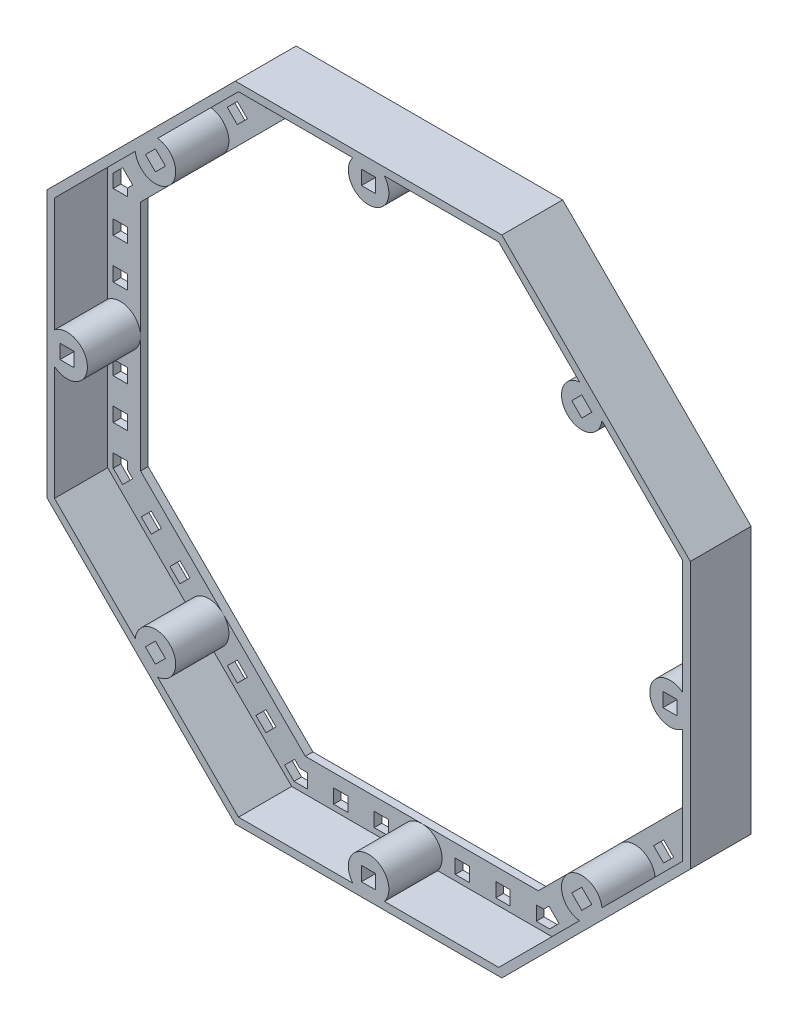
SolidWorks part; units mm, degrees
ref_plane "Plano frontal" through (0, 0, 0) normal (0, 0, 1) x (1, 0, 0)
ref_plane "Plano superior" through (0, 0, 0) normal (0, 1, 0) x (1, 0, 0)
ref_plane "Plano direito" through (0, 0, 0) normal (1, 0, 0) x (0, 0, -1)
sketch "Esboço1" plane through (0, 0, 0) normal (0, 0, 1) x (1, 0, 0)
  line L1 (63.5, -26.3026) -> (63.5, 26.3026)
  line L2 (63.5, 26.3026) -> (26.3026, 63.5)
  line L3 (26.3026, 63.5) -> (-26.3026, 63.5)
  line L4 (-26.3026, 63.5) -> (-63.5, 26.3026)
  line L5 (-63.5, 26.3026) -> (-63.5, -26.3026)
  line L6 (-63.5, -26.3026) -> (-26.3026, -63.5)
  line L7 (-26.3026, -63.5) -> (26.3026, -63.5)
  line L8 (26.3026, -63.5) -> (63.5, -26.3026)
  circle A0 centre (0, 0) radius 63.5 construction
  dimension "D1" = 127
extrude "Ressalto-extrusão1" add sketch "Esboço1" along normal blind 2.5
sketch "Esboço3"
sketch "Esboço2" plane through (0, 0, 0) normal (0, 0, -1) x (-1, 0, 0)
  line L0 (-42, 0) -> (42, 0) construction
  line L1 (-24, 0) -> (24, 0) construction
  line L3 (0, 0) -> (0, 75.734) construction
  line L4 (52.5, 24) -> (31.5, 24)
  line L5 (55.5, 21) -> (55.5, -21)
  line L6 (52.5, -24) -> (31.5, -24)
  line L7 (28.5, 21) -> (28.5, -21)
  line L8 (55.5, 24) -> (28.5, -24) construction
  line L9 (55.5, -24) -> (28.5, 24) construction
  line L10 (-55.5, -24) -> (-28.5, 24) construction
  line L11 (-55.5, 24) -> (-28.5, -24) construction
  line L13 (-28.5, 21) -> (-28.5, -21)
  line L14 (-52.5, -24) -> (-31.5, -24)
  line L15 (-55.5, 21) -> (-55.5, -21)
  line L16 (-52.5, 24) -> (-31.5, 24)
  line L17 (0, 0) -> (0, -57) construction
  line L19 (0, 63.5) -> (0, 43.5) construction
  line L20 (-26.3026, 63.5) -> (26.3026, 63.5) construction
  line L29 (63.5, 0) -> (-63.5, 0) construction
  line L30 (63.5, 26.3026) -> (63.5, -26.3026) construction
  line L31 (-63.5, -26.3026) -> (-63.5, 26.3026) construction
  arc A2 (31.5, 24) -> (28.5, 21) centre (31.5, 21) ccw
  arc A3 (31.5, -24) -> (28.5, -21) centre (31.5, -21) cw
  arc A4 (55.5, -21) -> (52.5, -24) centre (52.5, -21) cw
  arc A5 (52.5, 24) -> (55.5, 21) centre (52.5, 21) cw
  arc A6 (-52.5, 24) -> (-55.5, 21) centre (-52.5, 21) ccw
  arc A7 (-55.5, -21) -> (-52.5, -24) centre (-52.5, -21) ccw
  arc A8 (-31.5, -24) -> (-28.5, -21) centre (-31.5, -21) ccw
  arc A9 (-31.5, 24) -> (-28.5, 21) centre (-31.5, 21) cw
  dimension "D6" = 3
  dimension "D1" = 42
  dimension "D2" = 48
  dimension "D3" = 27
  dimension "D4" = 24
  dimension "D7" = 57
extrude "Corte-extrusão1" cut sketch "Esboço2" against normal through all
sketch "Esboço4" plane through (0, 0, 2.5) normal (0, 0, 1) x (1, 0, 0)
  line L0 (0, 0) -> (36.0624, 36.0624) construction
  line L1 (0, 0) -> (36.0624, -36.0624) construction
  line L2 (0, 0) -> (-36.0624, -36.0624) construction
  line L3 (0, 0) -> (-36.0624, 36.0624) construction
  line L4 (-38.0423, 36.0624) -> (-34.0825, 36.0624) construction
  line L11 (-36.0624, 34.0825) -> (-36.0624, 38.0423) construction
  line L12 (-36.0624, 34.0825) -> (-34.0825, 36.0624)
  line L13 (-38.0423, 36.0624) -> (-36.0624, 34.0825)
  line L14 (-36.0624, 38.0423) -> (-34.0825, 36.0624)
  line L15 (-38.0423, 36.0624) -> (-36.0624, 38.0423)
  line L16 (34.0825, 36.0624) -> (38.0423, 36.0624) construction
  line L17 (36.0624, 34.0825) -> (36.0624, 38.0423) construction
  line L18 (36.0624, 34.0825) -> (38.0423, 36.0624)
  line L19 (34.0825, 36.0624) -> (36.0624, 34.0825)
  line L20 (36.0624, 38.0423) -> (38.0423, 36.0624)
  line L21 (34.0825, 36.0624) -> (36.0624, 38.0423)
  line L22 (34.0825, -36.0624) -> (38.0423, -36.0624) construction
  line L23 (36.0624, -38.0423) -> (36.0624, -34.0825) construction
  line L24 (36.0624, -38.0423) -> (38.0423, -36.0624)
  line L25 (34.0825, -36.0624) -> (36.0624, -38.0423)
  line L26 (36.0624, -34.0825) -> (38.0423, -36.0624)
  line L27 (34.0825, -36.0624) -> (36.0624, -34.0825)
  line L28 (-38.0423, -36.0624) -> (-34.0825, -36.0624) construction
  line L29 (-36.0624, -38.0423) -> (-36.0624, -34.0825) construction
  line L30 (-36.0624, -38.0423) -> (-34.0825, -36.0624)
  line L31 (-38.0423, -36.0624) -> (-36.0624, -38.0423)
  line L32 (-36.0624, -34.0825) -> (-34.0825, -36.0624)
  line L33 (-38.0423, -36.0624) -> (-36.0624, -34.0825)
  circle A0 centre (0, 0) radius 51 construction
  circle A1 centre (-36.0624, 36.0624) radius 1.65 construction
  circle A2 centre (36.0624, 36.0624) radius 1.65 construction
  circle A3 centre (36.0624, -36.0624) radius 1.65 construction
  circle A4 centre (-36.0624, -36.0624) radius 1.65 construction
  point P10 (0, 0)
  point P17 (0, 0)
  point P21 (-36.0624, 36.0624)
  point P26 (36.0624, 36.0624)
  point P31 (36.0624, -36.0624)
  point P36 (-36.0624, -36.0624)
  dimension "D1" = 4
  dimension "D2" = 4
  dimension "D4" = 2.8
  dimension "D5" = 2.8
  dimension "D6" = 2.8
  dimension "D7" = 2.8
extrude "Corte-extrusão2" cut sketch "Esboço4" against normal blind 10.5
sketch "Esboço7" plane through (0, 0, 2.5) normal (0, 0, 1) x (1, 0, 0)
  line L0 (22.9889, -55.5) -> (55.5, -22.9889)
  line L1 (55.5, -22.9889) -> (55.5, 22.9889)
  line L2 (55.5, 22.9889) -> (22.9889, 55.5)
  line L3 (22.9889, 55.5) -> (-22.9889, 55.5)
  line L4 (-22.9889, 55.5) -> (-55.5, 22.9889)
  line L5 (-55.5, 22.9889) -> (-55.5, -22.9889)
  line L6 (-55.5, -22.9889) -> (-22.9889, -55.5)
  line L7 (-22.9889, -55.5) -> (22.9889, -55.5)
  line L8 (26.3026, -63.5) -> (63.5, -26.3026)
  line L9 (63.5, -26.3026) -> (63.5, 26.3026)
  line L10 (63.5, 26.3026) -> (26.3026, 63.5)
  line L11 (26.3026, 63.5) -> (-26.3026, 63.5)
  line L12 (-26.3026, 63.5) -> (-63.5, 26.3026)
  line L13 (-63.5, 26.3026) -> (-63.5, -26.3026)
  line L14 (-63.5, -26.3026) -> (-26.3026, -63.5)
  line L15 (-26.3026, -63.5) -> (26.3026, -63.5)
  line L16 (26.3026, -63.5) -> (63.5, -26.3026)
  line L17 (63.5, -26.3026) -> (63.5, 26.3026)
  line L18 (63.5, 26.3026) -> (26.3026, 63.5)
  line L19 (26.3026, 63.5) -> (-26.3026, 63.5)
  line L20 (-26.3026, 63.5) -> (-63.5, 26.3026)
  line L21 (-63.5, 26.3026) -> (-63.5, -26.3026)
  line L22 (-63.5, -26.3026) -> (-26.3026, -63.5)
  line L23 (-26.3026, -63.5) -> (26.3026, -63.5)
  dimension "D1" = 0
  dimension "D2" = 8
extrude "Ressalto-extrusão2" add sketch "Esboço7" along normal blind 9.5
sketch "Esboço5" plane through (0, 0, 0) normal (0, 0, -1) x (-1, 0, 0)
  line L0 (-44.9013, -44.9013) -> (-42.0729, -42.0729) construction
  line L1 (-26.3026, -63.5) -> (-63.5, -26.3026) construction
  line L2 (-47.7297, -34.4361) -> (-49.7096, -36.416)
  line L3 (-42.0729, -40.093) -> (-44.0528, -42.0729)
  line L4 (-42.0729, -40.093) -> (-40.093, -42.0729)
  line L5 (-40.093, -42.0729) -> (-42.0729, -44.0528)
  line L6 (-44.0528, -42.0729) -> (-42.0729, -44.0528)
  line L7 (-42.0729, -40.093) -> (-42.0729, -44.0528) construction
  line L8 (-40.093, -42.0729) -> (-44.0528, -42.0729) construction
  line L9 (-47.7297, -34.4361) -> (-45.7498, -36.416)
  line L10 (-45.7498, -36.416) -> (-47.7297, -38.3959)
  line L11 (-49.7096, -36.416) -> (-47.7297, -38.3959)
  line L12 (-47.7297, -34.4361) -> (-47.7297, -38.3959) construction
  line L13 (-45.7498, -36.416) -> (-49.7096, -36.416) construction
  line L14 (-53.3866, -28.7792) -> (-55.3665, -30.7591)
  line L15 (-53.3866, -28.7792) -> (-51.4067, -30.7591)
  line L16 (-51.4067, -30.7591) -> (-53.3866, -32.739)
  line L17 (-55.3665, -30.7591) -> (-53.3866, -32.739)
  line L18 (-53.3866, -28.7792) -> (-53.3866, -32.739) construction
  line L19 (-51.4067, -30.7591) -> (-55.3665, -30.7591) construction
  line L20 (-63.5, -26.3026) -> (-63.5, 26.3026) construction
  line L21 (63.5, 26.3026) -> (63.5, -26.3026) construction
  line L22 (-16, 24) -> (0, 24) construction
  line L23 (0, 24) -> (16, 24) construction
  line L24 (-9.4, 22.6) -> (-6.6, 25.4) construction
  line L25 (-9.4, 25.4) -> (-9.4, 22.6)
  line L26 (-9.4, 22.6) -> (-6.6, 22.6)
  line L27 (-9.4, 25.4) -> (-6.6, 22.6) construction
  line L28 (-30.7591, -51.4067) -> (-30.7591, -55.3665) construction
  line L29 (-28.7792, -53.3866) -> (-32.739, -53.3866) construction
  line L30 (-36.416, -45.7498) -> (-36.416, -49.7096) construction
  line L31 (-34.4361, -47.7297) -> (-38.3959, -47.7297) construction
  line L32 (-42.0729, -40.093) -> (-42.0729, -44.0528) construction
  line L33 (-40.093, -42.0729) -> (-44.0528, -42.0729) construction
  line L34 (-25.2256, -60.9) -> (-27.0822, -59.0434)
  line L35 (-25.1023, -57.0635) -> (-27.0822, -59.0434)
  line L36 (-9.4, 25.4) -> (-6.6, 25.4)
  line L37 (-6.6, 25.4) -> (-6.6, 22.6)
  line L38 (-30.7591, -55.3665) -> (-32.739, -53.3866)
  line L39 (-30.7591, -51.4067) -> (-32.739, -53.3866)
  line L40 (-28.7792, -53.3866) -> (-30.7591, -51.4067)
  line L41 (-28.7792, -53.3866) -> (-30.7591, -55.3665)
  line L42 (-36.416, -49.7096) -> (-38.3959, -47.7297)
  line L43 (-36.416, -45.7498) -> (-38.3959, -47.7297)
  line L44 (-34.4361, -47.7297) -> (-36.416, -45.7498)
  line L45 (-58.1, 6.6) -> (-60.9, 9.4) construction
  line L46 (-60.9, 6.6) -> (-58.1, 9.4) construction
  line L47 (-34.4361, -47.7297) -> (-36.416, -49.7096)
  line L48 (0, -63.5) -> (0, -59.5) construction
  line L49 (26.3026, -63.5) -> (-26.3026, -63.5) construction
  line L50 (-9.4, 6.6) -> (-6.6, 6.6)
  line L51 (1.4, -58.1) -> (-1.4, -58.1)
  line L52 (1.4, -58.1) -> (1.4, -60.9)
  line L53 (1.4, -60.9) -> (-1.4, -60.9)
  line L54 (-1.4, -58.1) -> (-1.4, -60.9)
  line L55 (1.4, -58.1) -> (-1.4, -60.9) construction
  line L56 (1.4, -60.9) -> (-1.4, -58.1) construction
  line L57 (-6.6, 9.4) -> (-6.6, 6.6)
  line L58 (-9.4, 9.4) -> (-6.6, 9.4)
  line L59 (-9.4, 9.4) -> (-9.4, 6.6)
  line L60 (-9.4, 6.6) -> (-6.6, 9.4) construction
  line L61 (-9.4, 9.4) -> (-6.6, 6.6) construction
  line L62 (-14.6, -58.1) -> (-17.4, -58.1)
  line L63 (-14.6, -58.1) -> (-14.6, -60.9)
  line L64 (-14.6, -60.9) -> (-17.4, -60.9)
  line L65 (-17.4, -58.1) -> (-17.4, -60.9)
  line L66 (-14.6, -58.1) -> (-17.4, -60.9) construction
  line L67 (-14.6, -60.9) -> (-17.4, -58.1) construction
  line L68 (-22.6, -58.1) -> (-24.0658, -58.1)
  line L69 (-22.6, -58.1) -> (-22.6, -60.9)
  line L70 (-22.6, -60.9) -> (-25.2256, -60.9)
  line L71 (6.6, 22.6) -> (9.4, 25.4) construction
  line L72 (6.6, 25.4) -> (6.6, 22.6)
  line L73 (6.6, 22.6) -> (9.4, 22.6)
  line L74 (6.6, 25.4) -> (9.4, 22.6) construction
  line L75 (6.6, 25.4) -> (9.4, 25.4)
  line L76 (9.4, 25.4) -> (9.4, 22.6)
  line L77 (-9.4, -1.4) -> (-6.6, -1.4)
  line L78 (-25.4, -58.1) -> (-25.4, -59.0434) [skipped]
  line L80 (-24.0658, -58.1) -> (-25.1023, -57.0635)
  line L82 (-23.5434, -59.0434) -> (-24, -59.5) construction
  line L83 (-25.4, 46.6) -> (-22.6, 49.4) construction
  line L84 (-24, -59.5) -> (-24.4566, -59.0434) construction
  line L85 (6.6, -25.4) -> (9.4, -22.6) construction
  line L86 (6.6, -22.6) -> (9.4, -25.4) construction
  line L87 (9.4, -25.4) -> (9.4, -22.6)
  line L88 (6.6, -25.4) -> (9.4, -25.4)
  line L89 (6.6, -22.6) -> (9.4, -22.6)
  line L90 (6.6, -25.4) -> (6.6, -22.6)
  line L91 (-9.4, -25.4) -> (-6.6, -22.6) construction
  line L92 (-9.4, -22.6) -> (-6.6, -25.4) construction
  line L93 (-6.6, -25.4) -> (-6.6, -22.6)
  line L94 (-9.4, -25.4) -> (-6.6, -25.4)
  line L95 (-9.4, -22.6) -> (-6.6, -22.6)
  line L96 (-9.4, -25.4) -> (-9.4, -22.6)
  line L97 (-60.25, 0) -> (60.25, 0) construction
  line L98 (0, 0) -> (0, 63.5) construction
  line L99 (-26.3026, 63.5) -> (26.3026, 63.5) construction
  line L100 (-25.4, 49.4) -> (-22.6, 46.6) construction
  line L101 (-6.6, 1.4) -> (-6.6, -1.4)
  line L102 (-9.4, 1.4) -> (-6.6, 1.4)
  line L103 (-9.4, 1.4) -> (-9.4, -1.4)
  line L104 (-9.4, -1.4) -> (-6.6, 1.4) construction
  line L105 (-9.4, 1.4) -> (-6.6, -1.4) construction
  line L106 (14.6, -60.9) -> (17.4, -58.1) construction
  line L107 (14.6, -58.1) -> (17.4, -60.9) construction
  line L108 (-9.4, -9.4) -> (-6.6, -9.4)
  line L109 (-6.6, -6.6) -> (-6.6, -9.4)
  line L110 (40.093, -42.0729) -> (44.0528, -42.0729) construction
  line L111 (42.0729, -40.093) -> (42.0729, -44.0528) construction
  line L112 (34.4361, -47.7297) -> (38.3959, -47.7297) construction
  line L113 (36.416, -45.7498) -> (36.416, -49.7096) construction
  line L114 (28.7792, -53.3866) -> (32.739, -53.3866) construction
  line L115 (30.7591, -51.4067) -> (30.7591, -55.3665) construction
  line L116 (-9.4, -6.6) -> (-6.6, -6.6)
  line L117 (-9.4, -6.6) -> (-9.4, -9.4)
  line L118 (-9.4, -9.4) -> (-6.6, -6.6) construction
  line L119 (51.4067, -30.7591) -> (55.3665, -30.7591) construction
  line L120 (53.3866, -28.7792) -> (53.3866, -32.739) construction
  line L121 (45.7498, -36.416) -> (49.7096, -36.416) construction
  line L122 (47.7297, -34.4361) -> (47.7297, -38.3959) construction
  line L123 (40.093, -42.0729) -> (44.0528, -42.0729) construction
  line L124 (42.0729, -40.093) -> (42.0729, -44.0528) construction
  line L125 (44.9013, -44.9013) -> (42.0729, -42.0729) construction
  line L126 (-9.4, -6.6) -> (-6.6, -9.4) construction
  line L127 (9.4, -6.6) -> (6.6, -9.4) construction
  line L128 (9.4, -9.4) -> (6.6, -6.6) construction
  line L129 (9.4, 1.4) -> (6.6, -1.4) construction
  line L130 (9.4, -1.4) -> (6.6, 1.4) construction
  line L131 (9.4, 9.4) -> (6.6, 6.6) construction
  line L132 (9.4, 6.6) -> (6.6, 9.4) construction
  line L133 (24.0658, -58.1) -> (25.1023, -57.0635)
  line L134 (60.9, -25.2256) -> (59.0434, -27.0822)
  line L135 (57.0635, -25.1023) -> (59.0434, -27.0822)
  line L136 (58.1, -6.6) -> (58.1, -9.4)
  line L137 (58.1, 1.4) -> (58.1, -1.4)
  line L138 (22.6, -60.9) -> (25.2256, -60.9)
  line L139 (22.6, -58.1) -> (22.6, -60.9)
  line L140 (22.6, -58.1) -> (24.0658, -58.1)
  line L141 (17.4, -58.1) -> (17.4, -60.9)
  line L142 (14.6, -60.9) -> (17.4, -60.9)
  line L143 (14.6, -58.1) -> (14.6, -60.9)
  line L144 (14.6, -58.1) -> (17.4, -58.1)
  line L145 (9.4, -6.6) -> (9.4, -9.4)
  line L146 (9.4, -6.6) -> (6.6, -6.6)
  line L147 (6.6, -6.6) -> (6.6, -9.4)
  line L148 (9.4, -9.4) -> (6.6, -9.4)
  line L149 (34.4361, -47.7297) -> (36.416, -49.7096)
  line L150 (40.093, -42.0729) -> (42.0729, -44.0528)
  line L151 (42.0729, -40.093) -> (44.0528, -42.0729)
  line L152 (34.4361, -47.7297) -> (36.416, -45.7498)
  line L153 (36.416, -45.7498) -> (38.3959, -47.7297)
  line L154 (36.416, -49.7096) -> (38.3959, -47.7297)
  line L155 (28.7792, -53.3866) -> (30.7591, -55.3665)
  line L156 (28.7792, -53.3866) -> (30.7591, -51.4067)
  line L157 (30.7591, -51.4067) -> (32.739, -53.3866)
  line L158 (30.7591, -55.3665) -> (32.739, -53.3866)
  line L159 (58.1, 1.4) -> (60.9, 1.4)
  line L160 (25.1023, -57.0635) -> (27.0822, -59.0434)
  line L161 (25.2256, -60.9) -> (27.0822, -59.0434)
  line L162 (60.9, 1.4) -> (60.9, -1.4)
  line L163 (58.1, -1.4) -> (60.9, -1.4)
  line L164 (58.1, -6.6) -> (60.9, -6.6)
  line L165 (60.9, -6.6) -> (60.9, -9.4)
  line L166 (55.3665, -30.7591) -> (53.3866, -32.739)
  line L167 (51.4067, -30.7591) -> (53.3866, -32.739)
  line L168 (53.3866, -28.7792) -> (51.4067, -30.7591)
  line L169 (53.3866, -28.7792) -> (55.3665, -30.7591)
  line L170 (49.7096, -36.416) -> (47.7297, -38.3959)
  line L171 (45.7498, -36.416) -> (47.7297, -38.3959)
  line L172 (47.7297, -34.4361) -> (45.7498, -36.416)
  line L173 (44.0528, -42.0729) -> (42.0729, -44.0528)
  line L174 (-58.1, 14.6) -> (-60.9, 17.4) construction
  line L175 (42.0729, -40.093) -> (40.093, -42.0729)
  line L176 (-60.9, 14.6) -> (-58.1, 17.4) construction
  line L177 (47.7297, -34.4361) -> (49.7096, -36.416)
  line L178 (44.9013, 44.9013) -> (42.0729, 42.0729) construction
  line L179 (42.0729, 40.093) -> (42.0729, 44.0528) construction
  line L180 (40.093, 42.0729) -> (44.0528, 42.0729) construction
  line L181 (47.7297, 34.4361) -> (47.7297, 38.3959) construction
  line L182 (45.7498, 36.416) -> (49.7096, 36.416) construction
  line L183 (53.3866, 28.7792) -> (53.3866, 32.739) construction
  line L184 (51.4067, 30.7591) -> (55.3665, 30.7591) construction
  line L185 (58.1, -9.4) -> (60.9, -9.4)
  line L186 (58.1, -14.6) -> (58.1, -17.4)
  line L187 (30.7591, 51.4067) -> (30.7591, 55.3665) construction
  line L188 (28.7792, 53.3866) -> (32.739, 53.3866) construction
  line L189 (36.416, 45.7498) -> (36.416, 49.7096) construction
  line L190 (34.4361, 47.7297) -> (38.3959, 47.7297) construction
  line L191 (42.0729, 40.093) -> (42.0729, 44.0528) construction
  line L192 (40.093, 42.0729) -> (44.0528, 42.0729) construction
  line L193 (9.4, 1.4) -> (9.4, -1.4)
  line L194 (9.4, 1.4) -> (6.6, 1.4)
  line L195 (14.6, 58.1) -> (17.4, 60.9) construction
  line L196 (14.6, 60.9) -> (17.4, 58.1) construction
  line L197 (58.1, -14.6) -> (60.9, -14.6)
  line L198 (60.9, -14.6) -> (60.9, -17.4)
  line L199 (58.1, -17.4) -> (60.9, -17.4)
  line L200 (58.1, -22.6) -> (58.1, -24.0658)
  line L201 (58.1, -22.6) -> (60.9, -22.6)
  line L202 (60.9, -22.6) -> (60.9, -25.2256)
  line L203 (58.1, -24.0658) -> (57.0635, -25.1023)
  line L204 (58.1, 24.0658) -> (57.0635, 25.1023)
  line L205 (-14.6, 60.9) -> (-17.4, 58.1) construction
  line L206 (-14.6, 58.1) -> (-17.4, 60.9) construction
  line L207 (6.6, 1.4) -> (6.6, -1.4)
  line L208 (9.4, -1.4) -> (6.6, -1.4)
  line L209 (1.4, 60.9) -> (-1.4, 58.1) construction
  line L210 (1.4, 58.1) -> (-1.4, 60.9) construction
  line L211 (0, 63.5) -> (0, 59.5) construction
  line L212 (-40.093, 42.0729) -> (-44.0528, 42.0729) construction
  line L213 (-42.0729, 40.093) -> (-42.0729, 44.0528) construction
  line L214 (-34.4361, 47.7297) -> (-38.3959, 47.7297) construction
  line L215 (-36.416, 45.7498) -> (-36.416, 49.7096) construction
  line L216 (-28.7792, 53.3866) -> (-32.739, 53.3866) construction
  line L217 (-30.7591, 51.4067) -> (-30.7591, 55.3665) construction
  line L218 (60.9, 22.6) -> (60.9, 25.2256)
  line L219 (58.1, 22.6) -> (60.9, 22.6)
  line L220 (-51.4067, 30.7591) -> (-55.3665, 30.7591) construction
  line L221 (-53.3866, 28.7792) -> (-53.3866, 32.739) construction
  line L222 (-45.7498, 36.416) -> (-49.7096, 36.416) construction
  line L223 (-47.7297, 34.4361) -> (-47.7297, 38.3959) construction
  line L224 (-40.093, 42.0729) -> (-44.0528, 42.0729) construction
  line L225 (-42.0729, 40.093) -> (-42.0729, 44.0528) construction
  line L226 (-44.9013, 44.9013) -> (-42.0729, 42.0729) construction
  line L227 (47.7297, 34.4361) -> (49.7096, 36.416)
  line L228 (42.0729, 40.093) -> (44.0528, 42.0729)
  line L229 (42.0729, 40.093) -> (40.093, 42.0729)
  line L230 (40.093, 42.0729) -> (42.0729, 44.0528)
  line L231 (44.0528, 42.0729) -> (42.0729, 44.0528)
  line L232 (47.7297, 34.4361) -> (45.7498, 36.416)
  line L233 (45.7498, 36.416) -> (47.7297, 38.3959)
  line L234 (49.7096, 36.416) -> (47.7297, 38.3959)
  line L235 (53.3866, 28.7792) -> (55.3665, 30.7591)
  line L236 (53.3866, 28.7792) -> (51.4067, 30.7591)
  line L237 (51.4067, 30.7591) -> (53.3866, 32.739)
  line L238 (55.3665, 30.7591) -> (53.3866, 32.739)
  line L239 (58.1, 22.6) -> (58.1, 24.0658)
  line L240 (58.1, 17.4) -> (60.9, 17.4)
  line L241 (60.9, 14.6) -> (60.9, 17.4)
  line L242 (58.1, 14.6) -> (60.9, 14.6)
  line L243 (25.2256, 60.9) -> (27.0822, 59.0434)
  line L244 (25.1023, 57.0635) -> (27.0822, 59.0434)
  line L245 (58.1, 14.6) -> (58.1, 17.4)
  line L246 (30.7591, 55.3665) -> (32.739, 53.3866)
  line L247 (30.7591, 51.4067) -> (32.739, 53.3866)
  line L248 (28.7792, 53.3866) -> (30.7591, 51.4067)
  line L249 (28.7792, 53.3866) -> (30.7591, 55.3665)
  line L250 (36.416, 49.7096) -> (38.3959, 47.7297)
  line L251 (36.416, 45.7498) -> (38.3959, 47.7297)
  line L252 (34.4361, 47.7297) -> (36.416, 45.7498)
  line L253 (-60.9, -14.6) -> (-58.1, -17.4) construction
  line L254 (-58.1, -14.6) -> (-60.9, -17.4) construction
  line L255 (34.4361, 47.7297) -> (36.416, 49.7096)
  line L256 (9.4, 9.4) -> (9.4, 6.6)
  line L257 (9.4, 9.4) -> (6.6, 9.4)
  line L258 (6.6, 9.4) -> (6.6, 6.6)
  line L259 (9.4, 6.6) -> (6.6, 6.6)
  line L260 (14.6, 58.1) -> (17.4, 58.1)
  line L261 (14.6, 58.1) -> (14.6, 60.9)
  line L262 (14.6, 60.9) -> (17.4, 60.9)
  line L263 (17.4, 58.1) -> (17.4, 60.9)
  line L264 (22.6, 58.1) -> (24.0658, 58.1)
  line L265 (22.6, 58.1) -> (22.6, 60.9)
  line L266 (22.6, 60.9) -> (25.2256, 60.9)
  line L267 (24.0658, 58.1) -> (25.1023, 57.0635)
  line L268 (58.1, 9.4) -> (60.9, 9.4)
  line L269 (60.9, 6.6) -> (60.9, 9.4)
  line L270 (58.1, 6.6) -> (60.9, 6.6)
  line L271 (58.1, 6.6) -> (58.1, 9.4)
  line L272 (57.0635, 25.1023) -> (59.0434, 27.0822)
  line L273 (60.9, 25.2256) -> (59.0434, 27.0822)
  line L274 (63.5, 0) -> (59.5, 0) construction
  line L275 (58.1, 1.4) -> (60.9, -1.4) construction
  line L276 (60.9, 1.4) -> (58.1, -1.4) construction
  line L277 (58.1, -6.6) -> (60.9, -9.4) construction
  line L278 (60.9, -6.6) -> (58.1, -9.4) construction
  line L279 (58.1, -14.6) -> (60.9, -17.4) construction
  line L280 (60.9, -14.6) -> (58.1, -17.4) construction
  line L281 (60.9, 14.6) -> (58.1, 17.4) construction
  line L282 (-24.0658, 58.1) -> (-25.1023, 57.0635)
  line L283 (-22.6, 60.9) -> (-25.2256, 60.9)
  line L284 (-22.6, 58.1) -> (-22.6, 60.9)
  line L285 (-22.6, 58.1) -> (-24.0658, 58.1)
  line L286 (-17.4, 58.1) -> (-17.4, 60.9)
  line L287 (-14.6, 60.9) -> (-17.4, 60.9)
  line L288 (-14.6, 58.1) -> (-14.6, 60.9)
  line L289 (-14.6, 58.1) -> (-17.4, 58.1)
  line L290 (-16, 59.5) -> (0, 59.5) construction
  line L291 (-9.4, 58.1) -> (-9.4, 60.9)
  line L292 (-6.6, 60.9) -> (-9.4, 58.1) construction
  line L293 (-1.4, 58.1) -> (-1.4, 60.9)
  line L294 (1.4, 60.9) -> (-1.4, 60.9)
  line L295 (1.4, 58.1) -> (1.4, 60.9)
  line L296 (1.4, 58.1) -> (-1.4, 58.1)
  line L297 (-6.6, 58.1) -> (-6.6, 60.9)
  line L298 (-34.4361, 47.7297) -> (-36.416, 49.7096)
  line L299 (-40.093, 42.0729) -> (-42.0729, 44.0528)
  line L300 (-42.0729, 40.093) -> (-44.0528, 42.0729)
  line L301 (-34.4361, 47.7297) -> (-36.416, 45.7498)
  line L302 (-36.416, 45.7498) -> (-38.3959, 47.7297)
  line L303 (-36.416, 49.7096) -> (-38.3959, 47.7297)
  line L304 (-28.7792, 53.3866) -> (-30.7591, 55.3665)
  line L305 (-28.7792, 53.3866) -> (-30.7591, 51.4067)
  line L306 (-30.7591, 51.4067) -> (-32.739, 53.3866)
  line L307 (-30.7591, 55.3665) -> (-32.739, 53.3866)
  line L308 (58.1, 14.6) -> (60.9, 17.4) construction
  line L309 (-25.1023, 57.0635) -> (-27.0822, 59.0434)
  line L310 (-25.2256, 60.9) -> (-27.0822, 59.0434)
  line L311 (60.9, 6.6) -> (58.1, 9.4) construction
  line L312 (58.1, 6.6) -> (60.9, 9.4) construction
  line L313 (-6.6, 60.9) -> (-9.4, 60.9)
  line L314 (-6.6, 58.1) -> (-9.4, 58.1)
  line L315 (-55.3665, 30.7591) -> (-53.3866, 32.739)
  line L316 (-51.4067, 30.7591) -> (-53.3866, 32.739)
  line L317 (-53.3866, 28.7792) -> (-51.4067, 30.7591)
  line L318 (-53.3866, 28.7792) -> (-55.3665, 30.7591)
  line L319 (-49.7096, 36.416) -> (-47.7297, 38.3959)
  line L320 (-45.7498, 36.416) -> (-47.7297, 38.3959)
  line L321 (-47.7297, 34.4361) -> (-45.7498, 36.416)
  line L322 (-44.0528, 42.0729) -> (-42.0729, 44.0528)
  line L323 (-60.9, -6.6) -> (-58.1, -9.4) construction
  line L324 (-42.0729, 40.093) -> (-40.093, 42.0729)
  line L325 (-58.1, -6.6) -> (-60.9, -9.4) construction
  line L326 (-47.7297, 34.4361) -> (-49.7096, 36.416)
  line L327 (-17.4, 46.6) -> (-14.6, 49.4) construction
  line L328 (1.4, 1.4) -> (-1.4, 1.4)
  line L329 (1.4, 1.4) -> (1.4, -1.4)
  line L330 (1.4, -1.4) -> (-1.4, -1.4)
  line L331 (-1.4, 1.4) -> (-1.4, -1.4)
  line L332 (1.4, 1.4) -> (-1.4, -1.4) construction
  line L333 (1.4, -1.4) -> (-1.4, 1.4) construction
  line L334 (-6.6, 58.1) -> (-9.4, 60.9) construction
  line L335 (6.6, 58.1) -> (9.4, 60.9) construction
  line L336 (6.6, 60.9) -> (9.4, 58.1) construction
  line L337 (6.6, 58.1) -> (9.4, 58.1)
  line L338 (6.6, 60.9) -> (9.4, 60.9)
  line L339 (6.6, 58.1) -> (6.6, 60.9)
  line L340 (9.4, 58.1) -> (9.4, 60.9)
  line L341 (6.6, -60.9) -> (9.4, -58.1) construction
  line L342 (6.6, -58.1) -> (9.4, -60.9) construction
  line L343 (9.4, -58.1) -> (9.4, -60.9)
  line L344 (6.6, -58.1) -> (6.6, -60.9)
  line L345 (25.4, 1.4) -> (22.6, -1.4) construction
  line L346 (25.4, -1.4) -> (22.6, 1.4) construction
  line L347 (25.4, 1.4) -> (25.4, -1.4)
  line L348 (25.4, 1.4) -> (22.6, 1.4)
  line L349 (22.6, 1.4) -> (22.6, -1.4)
  line L350 (25.4, -1.4) -> (22.6, -1.4)
  line L351 (33.4, 1.4) -> (30.6, -1.4) construction
  line L352 (33.4, -1.4) -> (30.6, 1.4) construction
  line L353 (33.4, 1.4) -> (33.4, -1.4) [skipped]
  line L354 (33.4, 1.4) -> (30.6, 1.4) [skipped]
  line L355 (30.6, 1.4) -> (30.6, -1.4) [skipped]
  line L356 (33.4, -1.4) -> (30.6, -1.4) [skipped]
  line L357 (41.4, 1.4) -> (38.6, -1.4) construction
  line L358 (41.4, -1.4) -> (38.6, 1.4) construction
  line L359 (41.4, 1.4) -> (41.4, -1.4) [skipped]
  line L360 (41.4, 1.4) -> (38.6, 1.4) [skipped]
  line L361 (38.6, 1.4) -> (38.6, -1.4) [skipped]
  line L362 (41.4, -1.4) -> (38.6, -1.4) [skipped]
  line L363 (49.4, 1.4) -> (46.6, -1.4) construction
  line L364 (49.4, -1.4) -> (46.6, 1.4) construction
  line L365 (49.4, 1.4) -> (49.4, -1.4) [skipped]
  line L366 (49.4, 1.4) -> (46.6, 1.4) [skipped]
  line L367 (46.6, 1.4) -> (46.6, -1.4) [skipped]
  line L368 (49.4, -1.4) -> (46.6, -1.4) [skipped]
  line L369 (6.6, -60.9) -> (9.4, -60.9)
  line L370 (6.6, -58.1) -> (9.4, -58.1)
  line L371 (-6.6, -58.1) -> (-9.4, -60.9) construction
  line L372 (-6.6, -60.9) -> (-9.4, -58.1) construction
  line L373 (-6.6, -58.1) -> (-9.4, -58.1)
  line L374 (-6.6, -60.9) -> (-9.4, -60.9)
  line L375 (-6.6, -58.1) -> (-6.6, -60.9)
  line L376 (-9.4, -58.1) -> (-9.4, -60.9)
  line L387 (33.4, 9.4) -> (30.6, 6.6) construction
  line L388 (33.4, 6.6) -> (30.6, 9.4) construction
  line L389 (33.4, 9.4) -> (33.4, 6.6) [skipped]
  line L390 (33.4, 9.4) -> (30.6, 9.4) [skipped]
  line L391 (30.6, 9.4) -> (30.6, 6.6) [skipped]
  line L392 (33.4, 6.6) -> (30.6, 6.6) [skipped]
  line L393 (41.4, 9.4) -> (38.6, 6.6) construction
  line L394 (41.4, 6.6) -> (38.6, 9.4) construction
  line L395 (41.4, 9.4) -> (41.4, 6.6) [skipped]
  line L396 (41.4, 9.4) -> (38.6, 9.4) [skipped]
  line L397 (38.6, 9.4) -> (38.6, 6.6) [skipped]
  line L398 (41.4, 6.6) -> (38.6, 6.6) [skipped]
  line L399 (49.4, 9.4) -> (46.6, 6.6) construction
  line L400 (49.4, 6.6) -> (46.6, 9.4) construction
  line L401 (49.4, 9.4) -> (49.4, 6.6) [skipped]
  line L402 (49.4, 9.4) -> (46.6, 9.4) [skipped]
  line L403 (46.6, 9.4) -> (46.6, 6.6) [skipped]
  line L404 (49.4, 6.6) -> (46.6, 6.6) [skipped]
  line L405 (9.4, 17.4) -> (6.6, 14.6) construction
  line L406 (9.4, 14.6) -> (6.6, 17.4) construction
  line L407 (9.4, 17.4) -> (9.4, 14.6)
  line L408 (9.4, 17.4) -> (6.6, 17.4)
  line L409 (6.6, 17.4) -> (6.6, 14.6)
  line L410 (9.4, 14.6) -> (6.6, 14.6)
  line L411 (17.4, 17.4) -> (14.6, 14.6) construction
  line L412 (17.4, 14.6) -> (14.6, 17.4) construction
  line L413 (17.4, 17.4) -> (17.4, 14.6) construction
  line L414 (17.4, 17.4) -> (14.6, 17.4) construction
  line L415 (14.6, 17.4) -> (14.6, 14.6) construction
  line L416 (17.4, 14.6) -> (14.6, 14.6) construction
  line L417 (25.4, 17.4) -> (22.6, 14.6) construction
  line L418 (25.4, 14.6) -> (22.6, 17.4) construction
  line L419 (25.4, 17.4) -> (25.4, 14.6)
  line L420 (25.4, 17.4) -> (22.6, 17.4)
  line L421 (22.6, 17.4) -> (22.6, 14.6)
  line L422 (25.4, 14.6) -> (22.6, 14.6)
  line L423 (33.4, 17.4) -> (30.6, 14.6) construction
  line L424 (33.4, 14.6) -> (30.6, 17.4) construction
  line L425 (33.4, 17.4) -> (33.4, 14.6) [skipped]
  line L426 (33.4, 17.4) -> (30.6, 17.4) [skipped]
  line L427 (30.6, 17.4) -> (30.6, 14.6) [skipped]
  line L428 (33.4, 14.6) -> (30.6, 14.6) [skipped]
  line L429 (41.4, 17.4) -> (38.6, 14.6) construction
  line L430 (41.4, 14.6) -> (38.6, 17.4) construction
  line L431 (41.4, 17.4) -> (41.4, 14.6) [skipped]
  line L432 (41.4, 17.4) -> (38.6, 17.4) [skipped]
  line L433 (38.6, 17.4) -> (38.6, 14.6) [skipped]
  line L434 (41.4, 14.6) -> (38.6, 14.6) [skipped]
  line L435 (49.4, 17.4) -> (46.6, 14.6) construction
  line L436 (49.4, 14.6) -> (46.6, 17.4) construction
  line L437 (49.4, 17.4) -> (49.4, 14.6) [skipped]
  line L438 (49.4, 17.4) -> (46.6, 17.4) [skipped]
  line L439 (46.6, 17.4) -> (46.6, 14.6) [skipped]
  line L440 (49.4, 14.6) -> (46.6, 14.6) [skipped]
  line L441 (9.4, 25.4) -> (6.6, 22.6) construction
  line L442 (9.4, 22.6) -> (6.6, 25.4) construction
  line L443 (9.4, 25.4) -> (9.4, 22.6) [skipped]
  line L444 (9.4, 25.4) -> (6.6, 25.4) [skipped]
  line L445 (6.6, 25.4) -> (6.6, 22.6) [skipped]
  line L446 (9.4, 22.6) -> (6.6, 22.6) [skipped]
  line L447 (17.4, 25.4) -> (14.6, 22.6) construction
  line L448 (17.4, 22.6) -> (14.6, 25.4) construction
  line L449 (17.4, 25.4) -> (17.4, 22.6)
  line L450 (17.4, 25.4) -> (14.6, 25.4)
  line L451 (14.6, 25.4) -> (14.6, 22.6)
  line L452 (17.4, 22.6) -> (14.6, 22.6)
  line L459 (33.4, 25.4) -> (30.6, 22.6) construction
  line L460 (33.4, 22.6) -> (30.6, 25.4) construction
  line L461 (33.4, 25.4) -> (33.4, 22.6) [skipped]
  line L462 (33.4, 25.4) -> (30.6, 25.4) [skipped]
  line L463 (30.6, 25.4) -> (30.6, 22.6) [skipped]
  line L464 (33.4, 22.6) -> (30.6, 22.6) [skipped]
  line L465 (41.4, 25.4) -> (38.6, 22.6) construction
  line L466 (41.4, 22.6) -> (38.6, 25.4) construction
  line L467 (41.4, 25.4) -> (41.4, 22.6) [skipped]
  line L468 (41.4, 25.4) -> (38.6, 25.4) [skipped]
  line L469 (38.6, 25.4) -> (38.6, 22.6) [skipped]
  line L470 (41.4, 22.6) -> (38.6, 22.6) [skipped]
  line L471 (49.4, 25.4) -> (46.6, 22.6) construction
  line L472 (49.4, 22.6) -> (46.6, 25.4) construction
  line L473 (49.4, 25.4) -> (49.4, 22.6) [skipped]
  line L474 (49.4, 25.4) -> (46.6, 25.4) [skipped]
  line L475 (46.6, 25.4) -> (46.6, 22.6) [skipped]
  line L476 (49.4, 22.6) -> (46.6, 22.6) [skipped]
  line L477 (9.4, 33.4) -> (6.6, 30.6) construction
  line L478 (9.4, 30.6) -> (6.6, 33.4) construction
  line L479 (9.4, 33.4) -> (9.4, 30.6)
  line L480 (9.4, 33.4) -> (6.6, 33.4)
  line L481 (6.6, 33.4) -> (6.6, 30.6)
  line L482 (9.4, 30.6) -> (6.6, 30.6)
  line L483 (17.4, 33.4) -> (14.6, 30.6) construction
  line L484 (17.4, 30.6) -> (14.6, 33.4) construction
  line L485 (17.4, 33.4) -> (17.4, 30.6)
  line L486 (17.4, 33.4) -> (14.6, 33.4)
  line L487 (14.6, 33.4) -> (14.6, 30.6)
  line L488 (17.4, 30.6) -> (14.6, 30.6)
  line L489 (25.4, 33.4) -> (22.6, 30.6) construction
  line L490 (25.4, 30.6) -> (22.6, 33.4) construction
  line L491 (25.4, 33.4) -> (25.4, 30.6)
  line L492 (25.4, 33.4) -> (22.6, 33.4)
  line L493 (22.6, 33.4) -> (22.6, 30.6)
  line L494 (25.4, 30.6) -> (22.6, 30.6)
  line L495 (33.4, 33.4) -> (30.6, 30.6) construction
  line L496 (33.4, 30.6) -> (30.6, 33.4) construction
  line L497 (33.4, 33.4) -> (33.4, 30.6)
  line L498 (33.4, 33.4) -> (30.6, 33.4)
  line L499 (30.6, 33.4) -> (30.6, 30.6)
  line L500 (33.4, 30.6) -> (30.6, 30.6)
  line L501 (41.4, 33.4) -> (38.6, 30.6) construction
  line L502 (41.4, 30.6) -> (38.6, 33.4) construction
  line L503 (41.4, 33.4) -> (41.4, 30.6)
  line L504 (41.4, 33.4) -> (38.6, 33.4)
  line L505 (38.6, 33.4) -> (38.6, 30.6)
  line L506 (41.4, 30.6) -> (38.6, 30.6)
  line L513 (9.4, 41.4) -> (6.6, 38.6) construction
  line L514 (9.4, 38.6) -> (6.6, 41.4) construction
  line L515 (9.4, 41.4) -> (9.4, 38.6)
  line L516 (9.4, 41.4) -> (6.6, 41.4)
  line L517 (6.6, 41.4) -> (6.6, 38.6)
  line L518 (9.4, 38.6) -> (6.6, 38.6)
  line L519 (17.4, 41.4) -> (14.6, 38.6) construction
  line L520 (17.4, 38.6) -> (14.6, 41.4) construction
  line L521 (17.4, 41.4) -> (17.4, 38.6)
  line L522 (17.4, 41.4) -> (14.6, 41.4)
  line L523 (14.6, 41.4) -> (14.6, 38.6)
  line L524 (17.4, 38.6) -> (14.6, 38.6)
  line L525 (25.4, 41.4) -> (22.6, 38.6) construction
  line L526 (25.4, 38.6) -> (22.6, 41.4) construction
  line L527 (25.4, 41.4) -> (25.4, 38.6)
  line L528 (25.4, 41.4) -> (22.6, 41.4)
  line L529 (22.6, 41.4) -> (22.6, 38.6)
  line L530 (25.4, 38.6) -> (22.6, 38.6)
  line L531 (33.4, 41.4) -> (30.6, 38.6) construction
  line L532 (33.4, 38.6) -> (30.6, 41.4) construction
  line L533 (33.4, 41.4) -> (33.4, 38.6)
  line L534 (33.4, 41.4) -> (30.6, 41.4)
  line L535 (30.6, 41.4) -> (30.6, 38.6)
  line L536 (33.4, 38.6) -> (30.6, 38.6)
  line L537 (41.4, 41.4) -> (38.6, 38.6) construction
  line L538 (41.4, 38.6) -> (38.6, 41.4) construction
  line L539 (41.4, 41.4) -> (41.4, 38.6) [skipped]
  line L540 (41.4, 41.4) -> (38.6, 41.4) [skipped]
  line L541 (38.6, 41.4) -> (38.6, 38.6) [skipped]
  line L542 (41.4, 38.6) -> (38.6, 38.6) [skipped]
  line L543 (49.4, 41.4) -> (46.6, 38.6) construction
  line L544 (49.4, 38.6) -> (46.6, 41.4) construction
  line L545 (49.4, 41.4) -> (49.4, 38.6) [skipped]
  line L546 (49.4, 41.4) -> (46.6, 41.4) [skipped]
  line L547 (46.6, 41.4) -> (46.6, 38.6) [skipped]
  line L548 (49.4, 38.6) -> (46.6, 38.6) [skipped]
  line L549 (9.4, 49.4) -> (6.6, 46.6) construction
  line L550 (9.4, 46.6) -> (6.6, 49.4) construction
  line L551 (9.4, 49.4) -> (9.4, 46.6)
  line L552 (9.4, 49.4) -> (6.6, 49.4)
  line L553 (6.6, 49.4) -> (6.6, 46.6)
  line L554 (9.4, 46.6) -> (6.6, 46.6)
  line L555 (17.4, 49.4) -> (14.6, 46.6) construction
  line L556 (17.4, 46.6) -> (14.6, 49.4) construction
  line L557 (17.4, 49.4) -> (17.4, 46.6)
  line L558 (17.4, 49.4) -> (14.6, 49.4)
  line L559 (14.6, 49.4) -> (14.6, 46.6)
  line L560 (17.4, 46.6) -> (14.6, 46.6)
  line L561 (25.4, 49.4) -> (22.6, 46.6) construction
  line L562 (25.4, 46.6) -> (22.6, 49.4) construction
  line L563 (25.4, 49.4) -> (25.4, 46.6)
  line L564 (25.4, 49.4) -> (22.6, 49.4)
  line L565 (22.6, 49.4) -> (22.6, 46.6)
  line L566 (25.4, 46.6) -> (22.6, 46.6)
  line L573 (41.4, 49.4) -> (38.6, 46.6) construction
  line L574 (41.4, 46.6) -> (38.6, 49.4) construction
  line L575 (41.4, 49.4) -> (41.4, 46.6) [skipped]
  line L576 (41.4, 49.4) -> (38.6, 49.4) [skipped]
  line L577 (38.6, 49.4) -> (38.6, 46.6) [skipped]
  line L578 (41.4, 46.6) -> (38.6, 46.6) [skipped]
  line L579 (49.4, 49.4) -> (46.6, 46.6) construction
  line L580 (49.4, 46.6) -> (46.6, 49.4) construction
  line L581 (49.4, 49.4) -> (49.4, 46.6) [skipped]
  line L582 (49.4, 49.4) -> (46.6, 49.4) [skipped]
  line L583 (46.6, 49.4) -> (46.6, 46.6) [skipped]
  line L584 (49.4, 46.6) -> (46.6, 46.6) [skipped]
  line L585 (1.4, 9.4) -> (-1.4, 6.6) construction
  line L586 (1.4, 6.6) -> (-1.4, 9.4) construction
  line L587 (1.4, 9.4) -> (1.4, 6.6)
  line L588 (1.4, 9.4) -> (-1.4, 9.4)
  line L589 (-1.4, 9.4) -> (-1.4, 6.6)
  line L590 (1.4, 6.6) -> (-1.4, 6.6)
  line L591 (1.4, 17.4) -> (-1.4, 14.6) construction
  line L592 (1.4, 14.6) -> (-1.4, 17.4) construction
  line L593 (1.4, 17.4) -> (1.4, 14.6)
  line L594 (1.4, 17.4) -> (-1.4, 17.4)
  line L595 (-1.4, 17.4) -> (-1.4, 14.6)
  line L596 (1.4, 14.6) -> (-1.4, 14.6)
  line L597 (1.4, 25.4) -> (-1.4, 22.6) construction
  line L598 (1.4, 22.6) -> (-1.4, 25.4) construction
  line L599 (1.4, 25.4) -> (1.4, 22.6)
  line L600 (1.4, 25.4) -> (-1.4, 25.4)
  line L601 (-1.4, 25.4) -> (-1.4, 22.6)
  line L602 (1.4, 22.6) -> (-1.4, 22.6)
  line L603 (1.4, 33.4) -> (-1.4, 30.6) construction
  line L604 (1.4, 30.6) -> (-1.4, 33.4) construction
  line L605 (1.4, 33.4) -> (1.4, 30.6)
  line L606 (1.4, 33.4) -> (-1.4, 33.4)
  line L607 (-1.4, 33.4) -> (-1.4, 30.6)
  line L608 (1.4, 30.6) -> (-1.4, 30.6)
  line L609 (1.4, 41.4) -> (-1.4, 38.6) construction
  line L610 (1.4, 38.6) -> (-1.4, 41.4) construction
  line L611 (1.4, 41.4) -> (1.4, 38.6)
  line L612 (1.4, 41.4) -> (-1.4, 41.4)
  line L613 (-1.4, 41.4) -> (-1.4, 38.6)
  line L614 (1.4, 38.6) -> (-1.4, 38.6)
  line L615 (1.4, 49.4) -> (-1.4, 46.6) construction
  line L616 (1.4, 46.6) -> (-1.4, 49.4) construction
  line L617 (1.4, 49.4) -> (1.4, 46.6)
  line L618 (1.4, 49.4) -> (-1.4, 49.4)
  line L619 (-1.4, 49.4) -> (-1.4, 46.6)
  line L620 (1.4, 46.6) -> (-1.4, 46.6)
  line L621 (-17.4, 49.4) -> (-14.6, 46.6) construction
  line L622 (-9.4, 46.6) -> (-6.6, 49.4) construction
  line L623 (-9.4, 49.4) -> (-6.6, 46.6) construction
  line L624 (-33.4, 38.6) -> (-30.6, 41.4) construction
  line L625 (-33.4, 41.4) -> (-30.6, 38.6) construction
  line L626 (-25.4, 38.6) -> (-22.6, 41.4) construction
  line L627 (-25.4, 41.4) -> (-22.6, 38.6) construction
  line L628 (-17.4, 38.6) -> (-14.6, 41.4) construction
  line L629 (-17.4, 41.4) -> (-14.6, 38.6) construction
  line L630 (-9.4, 38.6) -> (-6.6, 41.4) construction
  line L631 (-9.4, 41.4) -> (-6.6, 38.6) construction
  line L636 (-25.4, 46.6) -> (-22.6, 46.6)
  line L637 (-22.6, 49.4) -> (-22.6, 46.6)
  line L638 (-25.4, 49.4) -> (-22.6, 49.4)
  line L639 (-25.4, 49.4) -> (-25.4, 46.6)
  line L640 (-17.4, 46.6) -> (-14.6, 46.6)
  line L641 (-14.6, 49.4) -> (-14.6, 46.6)
  line L642 (-17.4, 49.4) -> (-14.6, 49.4)
  line L643 (-17.4, 49.4) -> (-17.4, 46.6)
  line L644 (-9.4, 46.6) -> (-6.6, 46.6)
  line L645 (-6.6, 49.4) -> (-6.6, 46.6)
  line L646 (-9.4, 49.4) -> (-6.6, 49.4)
  line L647 (-9.4, 49.4) -> (-9.4, 46.6)
  line L648 (-33.4, 38.6) -> (-30.6, 38.6)
  line L649 (-30.6, 41.4) -> (-30.6, 38.6)
  line L650 (-33.4, 41.4) -> (-30.6, 41.4)
  line L651 (-33.4, 41.4) -> (-33.4, 38.6)
  line L652 (-25.4, 38.6) -> (-22.6, 38.6)
  line L653 (-22.6, 41.4) -> (-22.6, 38.6)
  line L654 (-25.4, 41.4) -> (-22.6, 41.4)
  line L655 (-25.4, 41.4) -> (-25.4, 38.6)
  line L656 (-17.4, 38.6) -> (-14.6, 38.6)
  line L657 (-14.6, 41.4) -> (-14.6, 38.6)
  line L658 (-17.4, 41.4) -> (-14.6, 41.4)
  line L659 (-17.4, 41.4) -> (-17.4, 38.6)
  line L660 (-9.4, 38.6) -> (-6.6, 38.6)
  line L661 (-6.6, 41.4) -> (-6.6, 38.6)
  line L662 (-9.4, 41.4) -> (-6.6, 41.4)
  line L663 (-9.4, 41.4) -> (-9.4, 38.6)
  line L666 (-41.4, 30.6) -> (-38.6, 33.4) construction
  line L667 (-41.4, 33.4) -> (-38.6, 30.6) construction
  line L668 (-33.4, 30.6) -> (-30.6, 33.4) construction
  line L669 (-33.4, 33.4) -> (-30.6, 30.6) construction
  line L670 (-25.4, 30.6) -> (-22.6, 33.4) construction
  line L671 (-25.4, 33.4) -> (-22.6, 30.6) construction
  line L672 (-17.4, 30.6) -> (-14.6, 33.4) construction
  line L673 (-17.4, 33.4) -> (-14.6, 30.6) construction
  line L674 (-9.4, 30.6) -> (-6.6, 33.4) construction
  line L675 (-9.4, 33.4) -> (-6.6, 30.6) construction
  line L678 (-17.4, 22.6) -> (-14.6, 25.4) construction
  line L679 (-17.4, 25.4) -> (-14.6, 22.6) construction
  line L680 (-25.4, 14.6) -> (-22.6, 17.4) construction
  line L681 (-25.4, 17.4) -> (-22.6, 14.6) construction
  line L682 (-17.4, 14.6) -> (-14.6, 17.4) construction
  line L683 (-17.4, 17.4) -> (-14.6, 14.6) construction
  line L684 (-9.4, 14.6) -> (-6.6, 17.4) construction
  line L685 (-9.4, 17.4) -> (-6.6, 14.6) construction
  line L692 (-25.4, -1.4) -> (-22.6, 1.4) construction
  line L693 (-25.4, 1.4) -> (-22.6, -1.4) construction
  line L702 (-41.4, 30.6) -> (-38.6, 30.6)
  line L703 (-38.6, 33.4) -> (-38.6, 30.6)
  line L704 (-41.4, 33.4) -> (-38.6, 33.4)
  line L705 (-41.4, 33.4) -> (-41.4, 30.6)
  line L706 (-33.4, 30.6) -> (-30.6, 30.6)
  line L707 (-30.6, 33.4) -> (-30.6, 30.6)
  line L708 (-33.4, 33.4) -> (-30.6, 33.4)
  line L709 (-33.4, 33.4) -> (-33.4, 30.6)
  line L710 (-25.4, 30.6) -> (-22.6, 30.6)
  line L711 (-22.6, 33.4) -> (-22.6, 30.6)
  line L712 (-25.4, 33.4) -> (-22.6, 33.4)
  line L713 (-25.4, 33.4) -> (-25.4, 30.6)
  line L714 (-17.4, 30.6) -> (-14.6, 30.6)
  line L715 (-14.6, 33.4) -> (-14.6, 30.6)
  line L716 (-17.4, 33.4) -> (-14.6, 33.4)
  line L717 (-17.4, 33.4) -> (-17.4, 30.6)
  line L718 (-9.4, 30.6) -> (-6.6, 30.6)
  line L719 (-6.6, 33.4) -> (-6.6, 30.6)
  line L720 (-9.4, 33.4) -> (-6.6, 33.4)
  line L721 (-9.4, 33.4) -> (-9.4, 30.6)
  line L726 (-17.4, 22.6) -> (-14.6, 22.6)
  line L727 (-14.6, 25.4) -> (-14.6, 22.6)
  line L728 (-17.4, 25.4) -> (-14.6, 25.4)
  line L729 (-17.4, 25.4) -> (-17.4, 22.6)
  line L730 (-25.4, 14.6) -> (-22.6, 14.6)
  line L731 (-22.6, 17.4) -> (-22.6, 14.6)
  line L732 (-25.4, 17.4) -> (-22.6, 17.4)
  line L733 (-25.4, 17.4) -> (-25.4, 14.6)
  line L734 (-17.4, 14.6) -> (-14.6, 14.6) construction
  line L735 (-14.6, 17.4) -> (-14.6, 14.6) construction
  line L736 (-17.4, 17.4) -> (-14.6, 17.4) construction
  line L737 (-17.4, 17.4) -> (-17.4, 14.6) construction
  line L738 (-9.4, 14.6) -> (-6.6, 14.6)
  line L739 (-6.6, 17.4) -> (-6.6, 14.6)
  line L740 (-9.4, 17.4) -> (-6.6, 17.4)
  line L741 (-9.4, 17.4) -> (-9.4, 14.6)
  line L754 (-25.4, -1.4) -> (-22.6, -1.4)
  line L755 (-22.6, 1.4) -> (-22.6, -1.4)
  line L756 (-25.4, 1.4) -> (-22.6, 1.4)
  line L757 (-25.4, 1.4) -> (-25.4, -1.4)
  line L768 (41.4, -30.6) -> (38.6, -33.4) construction
  line L769 (41.4, -33.4) -> (38.6, -30.6) construction
  line L774 (41.4, -30.6) -> (38.6, -30.6)
  line L775 (38.6, -33.4) -> (38.6, -30.6)
  line L776 (41.4, -33.4) -> (38.6, -33.4)
  line L777 (41.4, -33.4) -> (41.4, -30.6)
  line L784 (-41.4, -33.4) -> (-38.6, -30.6) construction
  line L785 (-41.4, -30.6) -> (-38.6, -33.4) construction
  line L786 (-41.4, -33.4) -> (-41.4, -30.6)
  line L787 (-41.4, -33.4) -> (-38.6, -33.4)
  line L788 (-38.6, -33.4) -> (-38.6, -30.6)
  line L789 (-41.4, -30.6) -> (-38.6, -30.6)
  line L796 (-9.4, -17.4) -> (-6.6, -14.6) construction
  line L797 (-9.4, -14.6) -> (-6.6, -17.4) construction
  line L798 (-17.4, -17.4) -> (-14.6, -14.6) construction
  line L799 (-17.4, -14.6) -> (-14.6, -17.4) construction
  line L800 (-25.4, -17.4) -> (-22.6, -14.6) construction
  line L801 (-25.4, -14.6) -> (-22.6, -17.4) construction
  line L802 (-17.4, -25.4) -> (-14.6, -22.6) construction
  line L803 (-17.4, -22.6) -> (-14.6, -25.4) construction
  line L806 (-9.4, -33.4) -> (-6.6, -30.6) construction
  line L807 (-9.4, -30.6) -> (-6.6, -33.4) construction
  line L808 (-17.4, -33.4) -> (-14.6, -30.6) construction
  line L809 (-17.4, -30.6) -> (-14.6, -33.4) construction
  line L810 (-25.4, -33.4) -> (-22.6, -30.6) construction
  line L811 (-25.4, -30.6) -> (-22.6, -33.4) construction
  line L812 (-33.4, -33.4) -> (-30.6, -30.6) construction
  line L813 (-33.4, -30.6) -> (-30.6, -33.4) construction
  line L814 (-9.4, -41.4) -> (-6.6, -38.6) construction
  line L815 (-9.4, -38.6) -> (-6.6, -41.4) construction
  line L816 (-17.4, -41.4) -> (-14.6, -38.6) construction
  line L817 (-17.4, -38.6) -> (-14.6, -41.4) construction
  line L818 (-25.4, -41.4) -> (-22.6, -38.6) construction
  line L819 (-25.4, -38.6) -> (-22.6, -41.4) construction
  line L820 (-33.4, -41.4) -> (-30.6, -38.6) construction
  line L821 (-33.4, -38.6) -> (-30.6, -41.4) construction
  line L822 (-9.4, -49.4) -> (-6.6, -46.6) construction
  line L823 (-9.4, -46.6) -> (-6.6, -49.4) construction
  line L824 (-17.4, -49.4) -> (-14.6, -46.6) construction
  line L825 (1.4, -46.6) -> (-1.4, -49.4) construction
  line L826 (1.4, -49.4) -> (-1.4, -46.6) construction
  line L827 (1.4, -38.6) -> (-1.4, -41.4) construction
  line L828 (1.4, -41.4) -> (-1.4, -38.6) construction
  line L829 (1.4, -30.6) -> (-1.4, -33.4) construction
  line L830 (1.4, -33.4) -> (-1.4, -30.6) construction
  line L831 (1.4, -22.6) -> (-1.4, -25.4) construction
  line L832 (1.4, -25.4) -> (-1.4, -22.6) construction
  line L833 (1.4, -14.6) -> (-1.4, -17.4) construction
  line L834 (1.4, -17.4) -> (-1.4, -14.6) construction
  line L835 (1.4, -6.6) -> (-1.4, -9.4) construction
  line L836 (1.4, -9.4) -> (-1.4, -6.6) construction
  line L839 (25.4, -46.6) -> (22.6, -49.4) construction
  line L840 (25.4, -49.4) -> (22.6, -46.6) construction
  line L841 (17.4, -46.6) -> (14.6, -49.4) construction
  line L842 (17.4, -49.4) -> (14.6, -46.6) construction
  line L843 (9.4, -46.6) -> (6.6, -49.4) construction
  line L844 (9.4, -49.4) -> (6.6, -46.6) construction
  line L845 (33.4, -38.6) -> (30.6, -41.4) construction
  line L846 (33.4, -41.4) -> (30.6, -38.6) construction
  line L847 (25.4, -38.6) -> (22.6, -41.4) construction
  line L848 (25.4, -41.4) -> (22.6, -38.6) construction
  line L849 (17.4, -38.6) -> (14.6, -41.4) construction
  line L850 (17.4, -41.4) -> (14.6, -38.6) construction
  line L851 (9.4, -38.6) -> (6.6, -41.4) construction
  line L852 (9.4, -41.4) -> (6.6, -38.6) construction
  line L853 (33.4, -30.6) -> (30.6, -33.4) construction
  line L854 (33.4, -33.4) -> (30.6, -30.6) construction
  line L855 (25.4, -30.6) -> (22.6, -33.4) construction
  line L856 (25.4, -33.4) -> (22.6, -30.6) construction
  line L857 (17.4, -30.6) -> (14.6, -33.4) construction
  line L858 (17.4, -33.4) -> (14.6, -30.6) construction
  line L859 (9.4, -30.6) -> (6.6, -33.4) construction
  line L860 (9.4, -33.4) -> (6.6, -30.6) construction
  line L863 (17.4, -22.6) -> (14.6, -25.4) construction
  line L864 (17.4, -25.4) -> (14.6, -22.6) construction
  line L865 (25.4, -14.6) -> (22.6, -17.4) construction
  line L866 (25.4, -17.4) -> (22.6, -14.6) construction
  line L867 (17.4, -14.6) -> (14.6, -17.4) construction
  line L868 (17.4, -17.4) -> (14.6, -14.6) construction
  line L869 (9.4, -14.6) -> (6.6, -17.4) construction
  line L870 (9.4, -17.4) -> (6.6, -14.6) construction
  line L877 (-17.4, -46.6) -> (-14.6, -49.4) construction
  line L878 (-25.4, -49.4) -> (-22.6, -46.6) construction
  line L879 (-25.4, -46.6) -> (-22.6, -49.4) construction
  line L894 (-9.4, -17.4) -> (-9.4, -14.6)
  line L895 (-9.4, -17.4) -> (-6.6, -17.4)
  line L896 (-6.6, -17.4) -> (-6.6, -14.6)
  line L897 (-9.4, -14.6) -> (-6.6, -14.6)
  line L898 (-17.4, -17.4) -> (-17.4, -14.6) construction
  line L899 (-17.4, -17.4) -> (-14.6, -17.4) construction
  line L900 (-14.6, -17.4) -> (-14.6, -14.6) construction
  line L901 (-17.4, -14.6) -> (-14.6, -14.6) construction
  line L902 (-25.4, -17.4) -> (-25.4, -14.6)
  line L903 (-25.4, -17.4) -> (-22.6, -17.4)
  line L904 (-22.6, -17.4) -> (-22.6, -14.6)
  line L905 (-25.4, -14.6) -> (-22.6, -14.6)
  line L906 (-17.4, -25.4) -> (-17.4, -22.6)
  line L907 (-17.4, -25.4) -> (-14.6, -25.4)
  line L908 (-14.6, -25.4) -> (-14.6, -22.6)
  line L909 (-17.4, -22.6) -> (-14.6, -22.6)
  line L914 (-9.4, -33.4) -> (-9.4, -30.6)
  line L915 (-9.4, -33.4) -> (-6.6, -33.4)
  line L916 (-6.6, -33.4) -> (-6.6, -30.6)
  line L917 (-9.4, -30.6) -> (-6.6, -30.6)
  line L918 (-17.4, -33.4) -> (-17.4, -30.6)
  line L919 (-17.4, -33.4) -> (-14.6, -33.4)
  line L920 (-14.6, -33.4) -> (-14.6, -30.6)
  line L921 (-17.4, -30.6) -> (-14.6, -30.6)
  line L922 (-25.4, -33.4) -> (-25.4, -30.6)
  line L923 (-25.4, -33.4) -> (-22.6, -33.4)
  line L924 (-22.6, -33.4) -> (-22.6, -30.6)
  line L925 (-25.4, -30.6) -> (-22.6, -30.6)
  line L926 (-33.4, -33.4) -> (-33.4, -30.6)
  line L927 (-33.4, -33.4) -> (-30.6, -33.4)
  line L928 (-30.6, -33.4) -> (-30.6, -30.6)
  line L929 (-33.4, -30.6) -> (-30.6, -30.6)
  line L930 (-9.4, -41.4) -> (-9.4, -38.6)
  line L931 (-9.4, -41.4) -> (-6.6, -41.4)
  line L932 (-6.6, -41.4) -> (-6.6, -38.6)
  line L933 (-9.4, -38.6) -> (-6.6, -38.6)
  line L934 (-17.4, -41.4) -> (-17.4, -38.6)
  line L935 (-17.4, -41.4) -> (-14.6, -41.4)
  line L936 (-14.6, -41.4) -> (-14.6, -38.6)
  line L937 (-17.4, -38.6) -> (-14.6, -38.6)
  line L938 (-25.4, -41.4) -> (-25.4, -38.6)
  line L939 (-25.4, -41.4) -> (-22.6, -41.4)
  line L940 (-22.6, -41.4) -> (-22.6, -38.6)
  line L941 (-25.4, -38.6) -> (-22.6, -38.6)
  line L942 (-33.4, -41.4) -> (-33.4, -38.6)
  line L943 (-33.4, -41.4) -> (-30.6, -41.4)
  line L944 (-30.6, -41.4) -> (-30.6, -38.6)
  line L945 (-33.4, -38.6) -> (-30.6, -38.6)
  line L946 (-9.4, -49.4) -> (-9.4, -46.6)
  line L947 (-9.4, -49.4) -> (-6.6, -49.4)
  line L948 (-6.6, -49.4) -> (-6.6, -46.6)
  line L949 (-9.4, -46.6) -> (-6.6, -46.6)
  line L950 (-17.4, -49.4) -> (-17.4, -46.6)
  line L951 (-17.4, -49.4) -> (-14.6, -49.4)
  line L952 (-14.6, -49.4) -> (-14.6, -46.6)
  line L953 (-17.4, -46.6) -> (-14.6, -46.6)
  line L954 (-25.4, -49.4) -> (-25.4, -46.6)
  line L955 (-25.4, -49.4) -> (-22.6, -49.4)
  line L956 (-22.6, -49.4) -> (-22.6, -46.6)
  line L957 (-25.4, -46.6) -> (-22.6, -46.6)
  line L962 (1.4, -46.6) -> (-1.4, -46.6)
  line L963 (-1.4, -49.4) -> (-1.4, -46.6)
  line L964 (1.4, -49.4) -> (-1.4, -49.4)
  line L965 (1.4, -49.4) -> (1.4, -46.6)
  line L966 (1.4, -38.6) -> (-1.4, -38.6)
  line L967 (-1.4, -41.4) -> (-1.4, -38.6)
  line L968 (1.4, -41.4) -> (-1.4, -41.4)
  line L969 (1.4, -41.4) -> (1.4, -38.6)
  line L970 (1.4, -30.6) -> (-1.4, -30.6)
  line L971 (-1.4, -33.4) -> (-1.4, -30.6)
  line L972 (1.4, -33.4) -> (-1.4, -33.4)
  line L973 (1.4, -33.4) -> (1.4, -30.6)
  line L974 (1.4, -22.6) -> (-1.4, -22.6)
  line L975 (-1.4, -25.4) -> (-1.4, -22.6)
  line L976 (1.4, -25.4) -> (-1.4, -25.4)
  line L977 (1.4, -25.4) -> (1.4, -22.6)
  line L978 (1.4, -14.6) -> (-1.4, -14.6)
  line L979 (-1.4, -17.4) -> (-1.4, -14.6)
  line L980 (1.4, -17.4) -> (-1.4, -17.4)
  line L981 (1.4, -17.4) -> (1.4, -14.6)
  line L982 (1.4, -6.6) -> (-1.4, -6.6)
  line L983 (-1.4, -9.4) -> (-1.4, -6.6)
  line L984 (1.4, -9.4) -> (-1.4, -9.4)
  line L985 (1.4, -9.4) -> (1.4, -6.6)
  line L990 (25.4, -46.6) -> (22.6, -46.6)
  line L991 (22.6, -49.4) -> (22.6, -46.6)
  line L992 (25.4, -49.4) -> (22.6, -49.4)
  line L993 (25.4, -49.4) -> (25.4, -46.6)
  line L994 (17.4, -46.6) -> (14.6, -46.6)
  line L995 (14.6, -49.4) -> (14.6, -46.6)
  line L996 (17.4, -49.4) -> (14.6, -49.4)
  line L997 (17.4, -49.4) -> (17.4, -46.6)
  line L998 (9.4, -46.6) -> (6.6, -46.6)
  line L999 (6.6, -49.4) -> (6.6, -46.6)
  line L1000 (9.4, -49.4) -> (6.6, -49.4)
  line L1001 (9.4, -49.4) -> (9.4, -46.6)
  line L1002 (33.4, -38.6) -> (30.6, -38.6)
  line L1003 (30.6, -41.4) -> (30.6, -38.6)
  line L1004 (33.4, -41.4) -> (30.6, -41.4)
  line L1005 (33.4, -41.4) -> (33.4, -38.6)
  line L1006 (25.4, -38.6) -> (22.6, -38.6)
  line L1007 (22.6, -41.4) -> (22.6, -38.6)
  line L1008 (25.4, -41.4) -> (22.6, -41.4)
  line L1009 (25.4, -41.4) -> (25.4, -38.6)
  line L1010 (17.4, -38.6) -> (14.6, -38.6)
  line L1011 (14.6, -41.4) -> (14.6, -38.6)
  line L1012 (17.4, -41.4) -> (14.6, -41.4)
  line L1013 (17.4, -41.4) -> (17.4, -38.6)
  line L1014 (9.4, -38.6) -> (6.6, -38.6)
  line L1015 (6.6, -41.4) -> (6.6, -38.6)
  line L1016 (9.4, -41.4) -> (6.6, -41.4)
  line L1017 (9.4, -41.4) -> (9.4, -38.6)
  line L1018 (33.4, -30.6) -> (30.6, -30.6)
  line L1019 (30.6, -33.4) -> (30.6, -30.6)
  line L1020 (33.4, -33.4) -> (30.6, -33.4)
  line L1021 (33.4, -33.4) -> (33.4, -30.6)
  line L1022 (25.4, -30.6) -> (22.6, -30.6)
  line L1023 (22.6, -33.4) -> (22.6, -30.6)
  line L1024 (25.4, -33.4) -> (22.6, -33.4)
  line L1025 (25.4, -33.4) -> (25.4, -30.6)
  line L1026 (17.4, -30.6) -> (14.6, -30.6)
  line L1027 (14.6, -33.4) -> (14.6, -30.6)
  line L1028 (17.4, -33.4) -> (14.6, -33.4)
  line L1029 (17.4, -33.4) -> (17.4, -30.6)
  line L1030 (9.4, -30.6) -> (6.6, -30.6)
  line L1031 (6.6, -33.4) -> (6.6, -30.6)
  line L1032 (9.4, -33.4) -> (6.6, -33.4)
  line L1033 (9.4, -33.4) -> (9.4, -30.6)
  line L1038 (17.4, -22.6) -> (14.6, -22.6)
  line L1039 (14.6, -25.4) -> (14.6, -22.6)
  line L1040 (17.4, -25.4) -> (14.6, -25.4)
  line L1041 (17.4, -25.4) -> (17.4, -22.6)
  line L1042 (25.4, -14.6) -> (22.6, -14.6)
  line L1043 (22.6, -17.4) -> (22.6, -14.6)
  line L1044 (25.4, -17.4) -> (22.6, -17.4)
  line L1045 (25.4, -17.4) -> (25.4, -14.6)
  line L1046 (17.4, -14.6) -> (14.6, -14.6) construction
  line L1047 (14.6, -17.4) -> (14.6, -14.6) construction
  line L1048 (17.4, -17.4) -> (14.6, -17.4) construction
  line L1049 (17.4, -17.4) -> (17.4, -14.6) construction
  line L1050 (9.4, -14.6) -> (6.6, -14.6)
  line L1051 (6.6, -17.4) -> (6.6, -14.6)
  line L1052 (9.4, -17.4) -> (6.6, -17.4)
  line L1053 (9.4, -17.4) -> (9.4, -14.6)
  line L1066 (-60.9, 1.4) -> (-58.1, -1.4) construction
  line L1067 (-58.1, 1.4) -> (-60.9, -1.4) construction
  line L1068 (-63.5, 0) -> (-59.5, 0) construction
  line L1069 (-60.9, 25.2256) -> (-59.0434, 27.0822)
  line L1070 (-57.0635, 25.1023) -> (-59.0434, 27.0822)
  line L1071 (-58.1, 6.6) -> (-58.1, 9.4)
  line L1072 (-58.1, 6.6) -> (-60.9, 6.6)
  line L1073 (-60.9, 6.6) -> (-60.9, 9.4)
  line L1074 (-58.1, 9.4) -> (-60.9, 9.4)
  line L1075 (-58.1, 14.6) -> (-58.1, 17.4)
  line L1076 (-58.1, 14.6) -> (-60.9, 14.6)
  line L1077 (-60.9, 14.6) -> (-60.9, 17.4)
  line L1078 (-58.1, 17.4) -> (-60.9, 17.4)
  line L1079 (-58.1, 22.6) -> (-58.1, 24.0658)
  line L1080 (-58.1, 22.6) -> (-60.9, 22.6)
  line L1081 (-60.9, 22.6) -> (-60.9, 25.2256)
  line L1082 (-58.1, 24.0658) -> (-57.0635, 25.1023)
  line L1083 (-58.1, -24.0658) -> (-57.0635, -25.1023)
  line L1084 (-60.9, -22.6) -> (-60.9, -25.2256)
  line L1085 (-58.1, -22.6) -> (-60.9, -22.6)
  line L1086 (-58.1, -22.6) -> (-58.1, -24.0658)
  line L1087 (-58.1, -17.4) -> (-60.9, -17.4)
  line L1088 (-60.9, -14.6) -> (-60.9, -17.4)
  line L1089 (-58.1, -14.6) -> (-60.9, -14.6)
  line L1090 (-58.1, -14.6) -> (-58.1, -17.4)
  line L1091 (-58.1, -9.4) -> (-60.9, -9.4)
  line L1092 (-60.9, -6.6) -> (-60.9, -9.4)
  line L1093 (-58.1, -6.6) -> (-60.9, -6.6)
  line L1094 (-58.1, -1.4) -> (-60.9, -1.4)
  line L1095 (-60.9, 1.4) -> (-60.9, -1.4)
  line L1096 (-58.1, 1.4) -> (-60.9, 1.4)
  line L1097 (-58.1, 1.4) -> (-58.1, -1.4)
  line L1098 (-58.1, -6.6) -> (-58.1, -9.4)
  line L1099 (-57.0635, -25.1023) -> (-59.0434, -27.0822)
  line L1100 (-60.9, -25.2256) -> (-59.0434, -27.0822)
  line L1101 (-59.0434, -23.1224) -> (-61.0233, -25.1023) [skipped]
  line L1102 (-59.0434, -23.1224) -> (-57.0635, -25.1023) [skipped]
  line L1103 (-57.0635, -25.1023) -> (-59.0434, -27.0822) [skipped]
  line L1104 (-61.0233, -25.1023) -> (-59.0434, -27.0822) [skipped]
  line L1106 (-59.0434, -23.1224) -> (-59.0434, -27.0822) construction
  line L1107 (-57.0635, -25.1023) -> (-61.0233, -25.1023) construction
  line L1108 (25.4, 9.4) -> (25.4, 6.6) [skipped]
  line L1109 (25.4, 9.4) -> (22.6, 9.4) [skipped]
  line L1110 (22.6, 9.4) -> (22.6, 6.6) [skipped]
  line L1111 (25.4, 6.6) -> (22.6, 6.6) [skipped]
  line L1112 (25.4, 9.4) -> (22.6, 6.6) construction
  line L1113 (25.4, 6.6) -> (22.6, 9.4) construction
  line L1114 (-6.6, -58.1) -> (-9.4, -58.1) [skipped]
  line L1115 (-6.6, -58.1) -> (-6.6, -60.9) [skipped]
  line L1116 (-6.6, -60.9) -> (-9.4, -60.9) [skipped]
  line L1117 (-9.4, -58.1) -> (-9.4, -60.9) [skipped]
  line L1118 (-6.6, -58.1) -> (-9.4, -60.9) construction
  line L1119 (-6.6, -60.9) -> (-9.4, -58.1) construction
  line L1120 (9.4, 1.4) -> (9.4, -1.4) [skipped]
  line L1121 (9.4, 1.4) -> (6.6, 1.4) [skipped]
  line L1122 (6.6, 1.4) -> (6.6, -1.4) [skipped]
  line L1123 (9.4, -1.4) -> (6.6, -1.4) [skipped]
  line L1124 (17.4, 1.4) -> (17.4, -1.4) [skipped]
  line L1125 (17.4, 1.4) -> (14.6, 1.4) [skipped]
  line L1126 (14.6, 1.4) -> (14.6, -1.4) [skipped]
  line L1127 (17.4, -1.4) -> (14.6, -1.4) [skipped]
  line L1128 (9.4, 9.4) -> (9.4, 6.6) [skipped]
  line L1129 (9.4, 9.4) -> (6.6, 9.4) [skipped]
  line L1130 (6.6, 9.4) -> (6.6, 6.6) [skipped]
  line L1131 (9.4, 6.6) -> (6.6, 6.6) [skipped]
  line L1132 (17.4, 9.4) -> (17.4, 6.6) [skipped]
  line L1133 (17.4, 9.4) -> (14.6, 9.4) [skipped]
  line L1134 (14.6, 9.4) -> (14.6, 6.6) [skipped]
  line L1135 (17.4, 6.6) -> (14.6, 6.6) [skipped]
  line L1136 (9.4, 1.4) -> (6.6, -1.4) construction
  line L1137 (9.4, -1.4) -> (6.6, 1.4) construction
  line L1138 (17.4, 1.4) -> (14.6, -1.4) construction
  line L1139 (17.4, -1.4) -> (14.6, 1.4) construction
  line L1140 (9.4, 9.4) -> (6.6, 6.6) construction
  line L1141 (9.4, 6.6) -> (6.6, 9.4) construction
  line L1142 (17.4, 9.4) -> (14.6, 6.6) construction
  line L1143 (17.4, 6.6) -> (14.6, 9.4) construction
  line L1144 (33.4, 49.4) -> (33.4, 46.6) [skipped]
  line L1145 (33.4, 49.4) -> (30.6, 49.4) [skipped]
  line L1146 (30.6, 49.4) -> (30.6, 46.6) [skipped]
  line L1147 (33.4, 46.6) -> (30.6, 46.6) [skipped]
  line L1148 (33.4, 49.4) -> (30.6, 46.6) construction
  line L1149 (33.4, 46.6) -> (30.6, 49.4) construction
  line L1150 (49.4, 33.4) -> (49.4, 30.6) [skipped]
  line L1151 (49.4, 33.4) -> (46.6, 33.4) [skipped]
  line L1152 (46.6, 33.4) -> (46.6, 30.6) [skipped]
  line L1153 (49.4, 30.6) -> (46.6, 30.6) [skipped]
  line L1154 (49.4, 33.4) -> (46.6, 30.6) construction
  line L1155 (49.4, 30.6) -> (46.6, 33.4) construction
  line L1156 (25.4, 25.4) -> (25.4, 22.6) [skipped]
  line L1157 (25.4, 25.4) -> (22.6, 25.4) [skipped]
  line L1158 (22.6, 25.4) -> (22.6, 22.6) [skipped]
  line L1159 (25.4, 22.6) -> (22.6, 22.6) [skipped]
  line L1160 (25.4, 25.4) -> (22.6, 22.6) construction
  line L1161 (25.4, 22.6) -> (22.6, 25.4) construction
  point P4 (-42.0729, -42.0729)
  point P10 (-47.7297, -36.416)
  point P15 (-53.3866, -30.7591)
  point P20 (-63.5, 0)
  point P21 (-59.0434, -25.1023)
  point P22 (63.5, 0)
  point P36 (-25.1023, -59.0434)
  point P37 (-30.7591, -53.3866)
  point P38 (-36.416, -47.7297)
  point P44 (0, -59.5)
  point P52 (-8, -59.5)
  point P56 (-16, -59.5)
  point P61 (-24, -59.5)
  point P151 (24, -59.5)
  point P152 (16, -59.5)
  point P153 (-8, 59.5)
  point P154 (36.416, -47.7297)
  point P155 (30.7591, -53.3866)
  point P156 (25.1023, -59.0434)
  point P158 (53.3866, -30.7591)
  point P159 (47.7297, -36.416)
  point P215 (-8, 59.5)
  point P261 (47.7297, 36.416)
  point P262 (53.3866, 30.7591)
  point P264 (25.1023, 59.0434)
  point P265 (30.7591, 53.3866)
  point P266 (36.416, 47.7297)
  point P268 (16, 59.5)
  point P269 (24, 59.5)
  point P274 (-24, 59.5)
  point P275 (-16, 59.5)
  point P276 (8, 59.5)
  point P277 (-36.416, 47.7297)
  point P278 (-30.7591, 53.3866)
  point P279 (-25.1023, 59.0434)
  point P281 (-53.3866, 30.7591)
  point P282 (-47.7297, 36.416)
  point P294 (8, -59.5)
  point P315 (-8, -59.5)
  point P813 (-59.0434, 25.1023)
  point P814 (-59.5, 8)
  point P815 (-59.5, 16)
  point P816 (-59.5, 24)
  point P817 (-59.5, -24)
  point P818 (-59.5, -16)
  point P819 (-59.5, -8)
  point P820 (-59.0434, -25.1023)
  point P835 (59.0434, -25.1023)
  point P836 (59.5, -8)
  point P837 (59.5, -16)
  point P838 (59.5, -24)
  point P839 (59.5, 24)
  point P840 (59.5, 16)
  point P841 (59.5, 8)
  point P842 (59.0434, 25.1023)
  dimension "D1" = 4
  dimension "D2" = 2.8
  dimension "D3" = 2.8
  dimension "D5" = 4
  dimension "D6" = 7
  dimension "D7" = 7
  dimension "D4" = 4
extrude "Corte-extrusão3" cut sketch "Esboço5" against normal through all
sketch "Esboço8" plane through (0, 0, 2.5) normal (0, 0, 1) x (1, 0, 0)
  line L0 (-28.5, 21) -> (-28.5, -21) construction
  line L1 (-52.5, 24) -> (-31.5, 24) construction
  line L2 (-31.5, -24) -> (-52.5, -24) construction
  line L3 (-55.5, -21) -> (-55.5, 21) construction
  line L4 (-28.5, 21) -> (-28.5, -21)
  line L5 (-52.5, 24) -> (-31.5, 24)
  line L6 (-31.5, -24) -> (-52.5, -24)
  line L7 (-55.5, -21) -> (-55.5, 21)
  line L8 (0, 0) -> (0, -74.1657) construction
  line L9 (-28.5, 0) -> (-20.5, 0) construction
  line L10 (-42, 24) -> (-42, 25.5) construction
  line L11 (-42, -24) -> (-42, -25.5) construction
  line L12 (-42, -25.5) -> (-52.9889, -25.5)
  line L13 (-42, -25.5) -> (-30.5, -25.5)
  line L14 (-20.5, 0) -> (-20.5, -15.5)
  line L15 (-42, 25.5) -> (-52.9889, 25.5)
  line L16 (-42, 25.5) -> (-30.5, 25.5)
  line L17 (-20.5, 0) -> (-20.5, 15.5)
  line L18 (-22.9889, 55.5) -> (-55.5, 22.9889) construction
  line L19 (-55.5, 22.9889) -> (-55.5, 21) construction
  line L20 (-52.9889, 25.5) -> (-55.5, 22.9889)
  line L21 (-55.5, 22.9889) -> (-55.5, 21)
  line L22 (-55.5, -21) -> (-55.5, -22.9889) construction
  line L23 (-55.5, -22.9889) -> (-22.9889, -55.5) construction
  line L24 (-55.5, -21) -> (-55.5, -22.9889)
  line L25 (-55.5, -22.9889) -> (-52.9889, -25.5)
  line L26 (-25.4, 14.6) -> (-22.6, 14.6) construction
  line L27 (-25.4, 17.4) -> (-25.4, 14.6) construction
  line L28 (-22.6, 17.4) -> (-25.4, 17.4) construction
  line L29 (-22.6, 14.6) -> (-22.6, 17.4) construction
  line L30 (-25.4, 14.6) -> (-22.6, 14.6)
  line L31 (-25.4, 17.4) -> (-25.4, 14.6)
  line L32 (-22.6, 17.4) -> (-25.4, 17.4)
  line L33 (-22.6, 14.6) -> (-22.6, 17.4)
  line L34 (-25.4, 16) -> (-22.6, 16) construction
  line L35 (-25.4, 6.6) -> (-22.6, 6.6)
  line L36 (-25.4, 9.4) -> (-25.4, 6.6)
  line L37 (-22.6, 9.4) -> (-25.4, 9.4)
  line L38 (-22.6, 6.6) -> (-22.6, 9.4)
  line L39 (-25.4, 8) -> (-22.6, 8) construction
  line L40 (-25.4, -1.4) -> (-22.6, -1.4)
  line L41 (-25.4, 1.4) -> (-25.4, -1.4)
  line L42 (-22.6, 1.4) -> (-25.4, 1.4)
  line L43 (-22.6, -1.4) -> (-22.6, 1.4)
  line L44 (-25.4, 0) -> (-22.6, 0) construction
  line L45 (-25.4, -9.4) -> (-22.6, -9.4)
  line L46 (-25.4, -6.6) -> (-25.4, -9.4)
  line L47 (-22.6, -6.6) -> (-25.4, -6.6)
  line L48 (-22.6, -9.4) -> (-22.6, -6.6)
  line L49 (-25.4, -8) -> (-22.6, -8) construction
  line L50 (-25.4, -17.4) -> (-22.6, -17.4)
  line L51 (-25.4, -14.6) -> (-25.4, -17.4)
  line L52 (-22.6, -14.6) -> (-25.4, -14.6)
  line L53 (-22.6, -17.4) -> (-22.6, -14.6)
  line L54 (-25.4, -16) -> (-22.6, -16) construction
  line L55 (25.4, -16) -> (22.6, -16) construction
  line L56 (25.4, -8) -> (22.6, -8) construction
  line L57 (25.4, 0) -> (22.6, 0) construction
  line L58 (25.4, 8) -> (22.6, 8) construction
  line L59 (25.4, 16) -> (22.6, 16) construction
  line L60 (42, -24) -> (42, -25.5) construction
  line L61 (42, 24) -> (42, 25.5) construction
  line L62 (28.5, 0) -> (20.5, 0) construction
  line L63 (22.6, -17.4) -> (22.6, -14.6)
  line L64 (22.6, -14.6) -> (25.4, -14.6)
  line L65 (25.4, -14.6) -> (25.4, -17.4)
  line L66 (25.4, -17.4) -> (22.6, -17.4)
  line L67 (22.6, -9.4) -> (22.6, -6.6)
  line L68 (22.6, -6.6) -> (25.4, -6.6)
  line L69 (25.4, -6.6) -> (25.4, -9.4)
  line L70 (25.4, -9.4) -> (22.6, -9.4)
  line L71 (22.6, -1.4) -> (22.6, 1.4)
  line L72 (22.6, 1.4) -> (25.4, 1.4)
  line L73 (25.4, 1.4) -> (25.4, -1.4)
  line L74 (25.4, -1.4) -> (22.6, -1.4)
  line L75 (22.6, 6.6) -> (22.6, 9.4)
  line L76 (22.6, 9.4) -> (25.4, 9.4)
  line L77 (25.4, 9.4) -> (25.4, 6.6)
  line L78 (25.4, 6.6) -> (22.6, 6.6)
  line L79 (22.6, 14.6) -> (22.6, 17.4)
  line L80 (22.6, 17.4) -> (25.4, 17.4)
  line L81 (25.4, 17.4) -> (25.4, 14.6)
  line L82 (25.4, 14.6) -> (22.6, 14.6)
  line L83 (55.5, -22.9889) -> (52.9889, -25.5)
  line L84 (55.5, -21) -> (55.5, -22.9889)
  line L85 (55.5, 22.9889) -> (55.5, 21)
  line L86 (52.9889, 25.5) -> (55.5, 22.9889)
  line L87 (20.5, 0) -> (20.5, 15.5)
  line L88 (42, 25.5) -> (30.5, 25.5)
  line L89 (42, 25.5) -> (52.9889, 25.5)
  line L90 (20.5, 0) -> (20.5, -15.5)
  line L91 (42, -25.5) -> (30.5, -25.5)
  line L92 (42, -25.5) -> (52.9889, -25.5)
  line L93 (55.5, -21) -> (55.5, 21)
  line L94 (31.5, -24) -> (52.5, -24)
  line L95 (52.5, 24) -> (31.5, 24)
  line L96 (28.5, 21) -> (28.5, -21)
  arc A0 (-28.5, 21) -> (-31.5, 24) centre (-31.5, 21) ccw construction
  arc A1 (-31.5, -24) -> (-28.5, -21) centre (-31.5, -21) ccw construction
  arc A2 (-55.5, -21) -> (-52.5, -24) centre (-52.5, -21) ccw construction
  arc A3 (-28.5, 21) -> (-31.5, 24) centre (-31.5, 21) ccw
  arc A4 (-31.5, -24) -> (-28.5, -21) centre (-31.5, -21) ccw
  arc A5 (-55.5, -21) -> (-52.5, -24) centre (-52.5, -21) ccw
  arc A6 (-52.5, 24) -> (-55.5, 21) centre (-52.5, 21) ccw construction
  arc A7 (-52.5, 24) -> (-55.5, 21) centre (-52.5, 21) ccw
  arc A8 (-20.5, 15.5) -> (-30.5, 25.5) centre (-30.5, 15.5) ccw
  arc A9 (-20.5, -15.5) -> (-30.5, -25.5) centre (-30.5, -15.5) cw
  arc A10 (20.5, -15.5) -> (30.5, -25.5) centre (30.5, -15.5) ccw
  arc A11 (20.5, 15.5) -> (30.5, 25.5) centre (30.5, 15.5) cw
  arc A12 (52.5, 24) -> (55.5, 21) centre (52.5, 21) cw
  arc A13 (55.5, -21) -> (52.5, -24) centre (52.5, -21) cw
  arc A14 (31.5, -24) -> (28.5, -21) centre (31.5, -21) cw
  arc A15 (28.5, 21) -> (31.5, 24) centre (31.5, 21) cw
  point P39 (-24, 16)
  point P48 (-24, 8)
  point P55 (-24, 0)
  point P62 (-24, -8)
  point P69 (-24, -16)
  point P126 (24, -16)
  point P127 (24, -8)
  point P128 (24, 0)
  point P129 (24, 8)
  point P130 (24, 16)
  dimension "D1" = 10
  dimension "D2" = 5
extrude "Ressalto-extrusão3" add sketch "Esboço8" along normal up to surface (9.5 mm away) contours A9 L14 L17 A8 L16 L15 L20 L21 A7 L5 A3 L4 A4 L6 A5 L24 L25 L12 L13 L33 L30 L31 L32 L38 L35 L36 L37 L43 L40 L41 L42 L48 L45 L46 L47 L53 L50 L51 L52 | L96 A15 L95 A12 L85 L86 L89 L88 A11 L87 L90 A10 L91 L92 L83 L84 A13 L94 A14 L77 L78 L75 L76 L69 L70 L67 L68 L65 L66 L63 L64 L73 L74 L71 L72 L81 L82 L79 L80 region at (-28.0707, 0, 2.5) region at (28.0707, 0, 2.5) up to face at (59.0178, -24.446, 12)
sketch "Esboço9" plane through (0, 0, 2.5) normal (0, 0, 1) x (1, 0, 0)
  line L0 (0, 0) -> (0, -72.2465) construction
  line L1 (-25.4, 9.4) -> (-22.6, 9.4)
  line L2 (-25.4, -9.4) -> (-22.6, -9.4)
  line L3 (22.6, 6.6) -> (22.6, 9.4)
  line L4 (25.4, 6.6) -> (22.6, 6.6)
  line L5 (-25.4, -9.4) -> (-22.6, -9.4)
  line L7 (-22.6, -9.4) -> (-22.6, -6.6)
  line L8 (-22.6, -6.6) -> (-25.4, -6.6)
  line L9 (-25.4, -6.6) -> (-25.4, -9.4)
  line L10 (25.4, 9.4) -> (25.4, 6.6)
  line L11 (25.4, -6.6) -> (25.4, -9.4)
  line L12 (-22.6, -9.4) -> (-22.6, -6.6)
  line L13 (-22.6, -6.6) -> (-25.4, -6.6)
  line L14 (-25.4, -6.6) -> (-25.4, -9.4)
  line L15 (-22.6, 9.4) -> (-25.4, 9.4)
  line L16 (-25.4, 9.4) -> (-25.4, 6.6)
  line L17 (-25.4, 6.6) -> (-22.6, 6.6)
  line L18 (-22.6, 6.6) -> (-22.6, 9.4)
  line L20 (22.6, -6.6) -> (25.4, -6.6)
  line L21 (-25.4, 9.4) -> (-25.4, 6.6)
  line L22 (-25.4, 6.6) -> (-22.6, 6.6)
  line L23 (-22.6, 6.6) -> (-22.6, 9.4)
  line L24 (22.6, -9.4) -> (22.6, -6.6)
  line L25 (25.4, -9.4) -> (22.6, -9.4)
  line L26 (25.4, 9.4) -> (22.6, 9.4)
  line L28 (30.5, 25.5) -> (52.9889, 25.5)
  line L29 (52.9889, 25.5) -> (22.9889, 55.5)
  line L30 (22.9889, 55.5) -> (-22.9889, 55.5)
  line L31 (-22.9889, 55.5) -> (-52.9889, 25.5)
  line L32 (-52.9889, 25.5) -> (-30.5, 25.5)
  line L37 (-20.5, 15.5) -> (-20.5, -15.5)
  line L42 (-30.5, -25.5) -> (-52.9889, -25.5)
  line L43 (-52.9889, -25.5) -> (-22.9889, -55.5)
  line L44 (-22.9889, -55.5) -> (22.9889, -55.5)
  line L45 (22.9889, -55.5) -> (52.9889, -25.5)
  line L46 (52.9889, -25.5) -> (30.5, -25.5)
  line L51 (20.5, -15.5) -> (20.5, 15.5)
  line L56 (30.5, 25.5) -> (52.9889, 25.5)
  line L57 (52.9889, 25.5) -> (22.9889, 55.5)
  line L58 (22.9889, 55.5) -> (-22.9889, 55.5)
  line L59 (-22.9889, 55.5) -> (-52.9889, 25.5)
  line L60 (-52.9889, 25.5) -> (-30.5, 25.5)
  line L65 (-20.5, 15.5) -> (-20.5, -15.5)
  line L70 (-30.5, -25.5) -> (-52.9889, -25.5)
  line L71 (-52.9889, -25.5) -> (-22.9889, -55.5)
  line L72 (-22.9889, -55.5) -> (22.9889, -55.5)
  line L73 (22.9889, -55.5) -> (52.9889, -25.5)
  line L74 (52.9889, -25.5) -> (30.5, -25.5)
  line L79 (20.5, -15.5) -> (20.5, 15.5)
  arc A8 (-20.5, 15.5) -> (-30.5, 25.5) centre (-30.5, 15.5) ccw
  arc A10 (-30.5, -25.5) -> (-20.5, -15.5) centre (-30.5, -15.5) ccw
  arc A12 (20.5, -15.5) -> (30.5, -25.5) centre (30.5, -15.5) ccw
  arc A14 (30.5, 25.5) -> (20.5, 15.5) centre (30.5, 15.5) ccw
  arc A16 (-20.5, 15.5) -> (-30.5, 25.5) centre (-30.5, 15.5) ccw
  arc A18 (-30.5, -25.5) -> (-20.5, -15.5) centre (-30.5, -15.5) ccw
  arc A20 (20.5, -15.5) -> (30.5, -25.5) centre (30.5, -15.5) ccw
  arc A22 (30.5, 25.5) -> (20.5, 15.5) centre (30.5, 15.5) ccw
  dimension "D2" = 0
  dimension "D1" = 0
  dimension "D3" = 0
extrude "Corte-extrusão4" cut sketch "Esboço9" against normal through all
sketch "Esboço11" plane through (0, 0, 0) normal (0, 0, -1) x (-1, 0, 0)
  line L0 (-55.5, 21) -> (-55.5, -21) construction
  line L1 (-52.5, -24) -> (-31.5, -24) construction
  line L2 (-28.5, -21) -> (-28.5, 21) construction
  line L3 (-31.5, 24) -> (-52.5, 24) construction
  line L4 (-55.5, 21) -> (-55.5, -21)
  line L5 (-52.5, -24) -> (-31.5, -24)
  line L6 (-28.5, -21) -> (-28.5, 21)
  line L7 (-31.5, 24) -> (-52.5, 24)
  line L8 (0, 0) -> (0, 75.9676) construction
  line L9 (31.5, 24) -> (52.5, 24)
  line L10 (28.5, -21) -> (28.5, 21)
  line L11 (52.5, -24) -> (31.5, -24)
  line L12 (55.5, 21) -> (55.5, -21)
  arc A0 (-52.5, 24) -> (-55.5, 21) centre (-52.5, 21) ccw construction
  arc A1 (-55.5, -21) -> (-52.5, -24) centre (-52.5, -21) ccw construction
  arc A2 (-31.5, -24) -> (-28.5, -21) centre (-31.5, -21) ccw construction
  arc A3 (-28.5, 21) -> (-31.5, 24) centre (-31.5, 21) ccw construction
  arc A4 (-52.5, 24) -> (-55.5, 21) centre (-52.5, 21) ccw
  arc A5 (-55.5, -21) -> (-52.5, -24) centre (-52.5, -21) ccw
  arc A6 (-31.5, -24) -> (-28.5, -21) centre (-31.5, -21) ccw
  arc A7 (-28.5, 21) -> (-31.5, 24) centre (-31.5, 21) ccw
  arc A8 (28.5, 21) -> (31.5, 24) centre (31.5, 21) cw
  arc A9 (31.5, -24) -> (28.5, -21) centre (31.5, -21) cw
  arc A10 (55.5, -21) -> (52.5, -24) centre (52.5, -21) cw
  arc A11 (52.5, 24) -> (55.5, 21) centre (52.5, 21) cw
extrude "Ressalto-extrusão4" add sketch "Esboço11" against normal blind 1
sketch "Esboço12" plane through (0, 0, 0) normal (0, 0, -1) x (-1, 0, 0)
  line L1 (-22.9889, -55.5) -> (22.9889, -55.5)
  line L2 (22.9889, -55.5) -> (55.5, -22.9889)
  line L3 (55.5, -22.9889) -> (55.5, 22.9889)
  line L4 (55.5, 22.9889) -> (22.9889, 55.5)
  line L5 (22.9889, 55.5) -> (-22.9889, 55.5)
  line L6 (-22.9889, 55.5) -> (-55.5, 22.9889)
  line L7 (-55.5, 22.9889) -> (-55.5, -22.9889)
  line L8 (-55.5, -22.9889) -> (-22.9889, -55.5)
  circle A0 centre (0, 0) radius 55.5 construction
extrude "Corte-extrusão5" cut sketch "Esboço12" against normal through all
sketch "Esboço13" plane through (0, 0, 12) normal (0, 0, 1) x (1, 0, 0)
  line L24 (-62, 25.6812) -> (-62, -25.6812)
  line L25 (-62, -25.6812) -> (-25.6812, -62)
  line L26 (-25.6812, -62) -> (25.6812, -62)
  line L27 (25.6812, -62) -> (62, -25.6812)
  line L28 (62, -25.6812) -> (62, 25.6812)
  line L29 (62, 25.6812) -> (25.6812, 62)
  line L30 (25.6812, 62) -> (-25.6812, 62)
  line L31 (-25.6812, 62) -> (-62, 25.6812)
  line L32 (-62, 25.6812) -> (-62, -25.6812)
  line L33 (-62, -25.6812) -> (-25.6812, -62)
  line L34 (-25.6812, -62) -> (25.6812, -62)
  line L35 (25.6812, -62) -> (62, -25.6812)
  line L36 (62, -25.6812) -> (62, 25.6812)
  line L37 (62, 25.6812) -> (25.6812, 62)
  line L38 (25.6812, 62) -> (-25.6812, 62)
  line L39 (-25.6812, 62) -> (-62, 25.6812)
  dimension "D1" = 1.5
extrude "Corte-extrusão6" cut sketch "Esboço13" against normal blind 10.5
sketch "Esboço14" plane through (0, 0, 1.5) normal (0, 0, 1) x (1, 0, 0)
  line L0 (0, 58.1) -> (0, 60.9) construction
  line L1 (1.4, 58.1) -> (-1.4, 58.1) construction
  line L2 (-1.4, 60.9) -> (1.4, 60.9) construction
  line L3 (1.4, 60.9) -> (1.4, 58.1) construction
  line L4 (-1.4, 58.1) -> (-1.4, 60.9) construction
  line L5 (1.4, 58.1) -> (-1.4, 58.1)
  line L6 (1.4, 60.9) -> (1.4, 58.1)
  line L7 (-1.4, 60.9) -> (1.4, 60.9)
  line L8 (-1.4, 58.1) -> (-1.4, 60.9)
  line L9 (42.0729, 40.093) -> (40.093, 42.0729)
  line L10 (44.0528, 42.0729) -> (42.0729, 40.093)
  line L11 (42.0729, 44.0528) -> (44.0528, 42.0729)
  line L12 (40.093, 42.0729) -> (42.0729, 44.0528)
  line L13 (41.0829, 41.0829) -> (43.0628, 43.0628) construction
  line L14 (58.1, -1.4) -> (58.1, 1.4)
  line L15 (60.9, -1.4) -> (58.1, -1.4)
  line L16 (60.9, 1.4) -> (60.9, -1.4)
  line L17 (58.1, 1.4) -> (60.9, 1.4)
  line L18 (58.1, 0) -> (60.9, 0) construction
  line L19 (40.093, -42.0729) -> (42.0729, -40.093)
  line L20 (42.0729, -44.0528) -> (40.093, -42.0729)
  line L21 (44.0528, -42.0729) -> (42.0729, -44.0528)
  line L22 (42.0729, -40.093) -> (44.0528, -42.0729)
  line L23 (41.0829, -41.0829) -> (43.0628, -43.0628) construction
  line L24 (-1.4, -58.1) -> (1.4, -58.1)
  line L25 (-1.4, -60.9) -> (-1.4, -58.1)
  line L26 (1.4, -60.9) -> (-1.4, -60.9)
  line L27 (1.4, -58.1) -> (1.4, -60.9)
  line L28 (0, -58.1) -> (0, -60.9) construction
  line L29 (-42.0729, -40.093) -> (-40.093, -42.0729)
  line L30 (-44.0528, -42.0729) -> (-42.0729, -40.093)
  line L31 (-42.0729, -44.0528) -> (-44.0528, -42.0729)
  line L32 (-40.093, -42.0729) -> (-42.0729, -44.0528)
  line L33 (-41.0829, -41.0829) -> (-43.0628, -43.0628) construction
  line L34 (-58.1, 1.4) -> (-58.1, -1.4)
  line L35 (-60.9, 1.4) -> (-58.1, 1.4)
  line L36 (-60.9, -1.4) -> (-60.9, 1.4)
  line L37 (-58.1, -1.4) -> (-60.9, -1.4)
  line L38 (-58.1, 0) -> (-60.9, 0) construction
  line L39 (-40.093, 42.0729) -> (-42.0729, 40.093)
  line L40 (-42.0729, 44.0528) -> (-40.093, 42.0729)
  line L41 (-44.0528, 42.0729) -> (-42.0729, 44.0528)
  line L42 (-42.0729, 40.093) -> (-44.0528, 42.0729)
  line L43 (-41.0829, 41.0829) -> (-43.0628, 43.0628) construction
  circle A0 centre (0, 59.5) radius 4
  circle A1 centre (42.0729, 42.0729) radius 4
  circle A2 centre (59.5, 0) radius 4
  circle A3 centre (42.0729, -42.0729) radius 4
  circle A4 centre (0, -59.5) radius 4
  circle A5 centre (-42.0729, -42.0729) radius 4
  circle A6 centre (-59.5, 0) radius 4
  circle A7 centre (-42.0729, 42.0729) radius 4
  point P66 (0, 0)
  dimension "D1" = 8
extrude "Ressalto-extrusão6" add sketch "Esboço14" along normal up to surface (10.5 mm away) up to face at (0, 0, 12)
